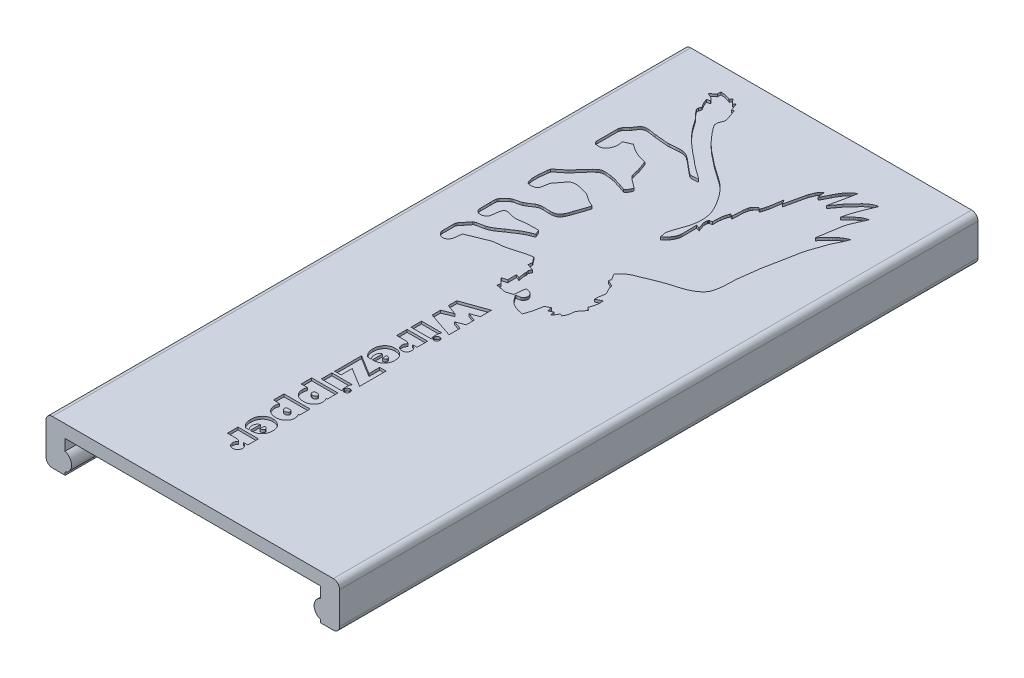
SolidWorks part; units mm, degrees
ref_plane "Front Plane" through (0, 0, 0) normal (0, 0, 1) x (1, 0, 0)
ref_plane "Top Plane" through (0, 0, 0) normal (0, 1, 0) x (1, 0, 0)
ref_plane "Right Plane" through (0, 0, 0) normal (1, 0, 0) x (0, 0, -1)
sketch "Sketch1" plane through (0, 0, 0) normal (0, 0, 1) x (1, 0, 0)
  line L0 (21.5, 0) -> (22.5, 0)
  line L1 (0.5, 0) -> (1.5, 0)
  line L2 (0, 0.5) -> (0, 3)
  line L3 (0.5, 3.5) -> (22.5, 3.5)
  line L4 (23, 0.5) -> (23, 3)
  line L5 (1.5, 2.5) -> (21.5, 2.5)
  line L6 (1.5, 2.5) -> (1.5, 1.637)
  line L8 (21.5, 2.5) -> (21.5, 1.637)
  line L9 (1.5, 0.2228) -> (1.5, 0)
  line L10 (1.25, 0.9299) -> (21.75, 0.9299) construction
  line L11 (21.5, 0.2228) -> (21.5, 0)
  arc A1 (1.5, 0.2228) -> (1.5, 1.637) centre (1.25, 0.9299) ccw
  arc A2 (21.5, 1.637) -> (21.5, 0.2228) centre (21.75, 0.9299) ccw
  arc A3 (23, 3) -> (22.5, 3.5) centre (22.5, 3) ccw
  arc A4 (0.5, 3.5) -> (0, 3) centre (0.5, 3) ccw
  arc A5 (23, 0.5) -> (22.5, 0) centre (22.5, 0.5) cw
  arc A6 (0, 0.5) -> (0.5, 0) centre (0.5, 0.5) ccw
  point P9 (11.5, 2.5)
  point P10 (11.5, 3.5)
  point P11 (0, 1.75)
  point P20 (23, 3.5)
  point P23 (0, 3.5)
  point P28 (0, 0)
  dimension "D6" = 1.5
  dimension "D9" = 0.5
  dimension "D10" = 0.5
  dimension "D1" = 23
  dimension "D2" = 3.5
  dimension "D3" = 1
  dimension "D4" = 1.5
  dimension "D5" = 20
  dimension "D7" = 0.25
  dimension "D8" = 0.25
extrude "Boss-Extrude1" add sketch "Sketch1" along normal blind 50
sketch "Sketch2" plane through (0, 3.5, -61.2632) normal (0, 1, 0) x (1, 0, 0)
  line L4 (19.7713, -68.0162) -> (19.7056, -68.0387)
  line L5 (19.7056, -68.0387) -> (19.6414, -68.0638)
  line L6 (19.6414, -68.0638) -> (19.5786, -68.0912)
  line L7 (19.5786, -68.0912) -> (19.5173, -68.1208)
  line L8 (19.5173, -68.1208) -> (19.4572, -68.1527)
  line L9 (19.4572, -68.1527) -> (19.3985, -68.1865)
  line L10 (19.3985, -68.1865) -> (19.341, -68.2223)
  line L11 (19.341, -68.2223) -> (19.2846, -68.2598)
  line L12 (19.2846, -68.2598) -> (19.2294, -68.2991)
  line L13 (19.2294, -68.2991) -> (19.1752, -68.34)
  line L14 (19.1752, -68.34) -> (19.122, -68.3824)
  line L15 (19.122, -68.3824) -> (19.0697, -68.4261)
  line L16 (19.0697, -68.4261) -> (19.0184, -68.4711)
  line L17 (19.0184, -68.4711) -> (18.918, -68.5644)
  line L18 (18.918, -68.5644) -> (18.7727, -68.711)
  line L19 (18.7727, -68.711) -> (18.2698, -69.2714)
  line L20 (18.2698, -69.2714) -> (18.2812, -69.1529)
  line L21 (18.2812, -69.1529) -> (18.535, -67.5691)
  line L22 (18.535, -67.5691) -> (18.544, -67.5095)
  line L23 (18.544, -67.5095) -> (18.5547, -67.4504)
  line L24 (18.5547, -67.4504) -> (18.567, -67.3918)
  line L25 (18.567, -67.3918) -> (18.5808, -67.3338)
  line L26 (18.5808, -67.3338) -> (18.6125, -67.2189)
  line L27 (18.6125, -67.2189) -> (18.649, -67.1057)
  line L28 (18.649, -67.1057) -> (18.7112, -66.9383)
  line L29 (18.7112, -66.9383) -> (19.0474, -66.172)
  line L30 (19.0474, -66.172) -> (19.1337, -65.9499)
  line L31 (19.1337, -65.9499) -> (19.0766, -65.96)
  line L32 (19.0766, -65.96) -> (19.021, -65.9729)
  line L33 (19.021, -65.9729) -> (18.9668, -65.9885)
  line L34 (18.9668, -65.9885) -> (18.9139, -66.0067)
  line L35 (18.9139, -66.0067) -> (18.8624, -66.0273)
  line L36 (18.8624, -66.0273) -> (18.812, -66.0502)
  line L37 (18.812, -66.0502) -> (18.7628, -66.0753)
  line L38 (18.7628, -66.0753) -> (18.7147, -66.1024)
  line L39 (18.7147, -66.1024) -> (18.6677, -66.1313)
  line L40 (18.6677, -66.1313) -> (18.6216, -66.1621)
  line L41 (18.6216, -66.1621) -> (18.5764, -66.1944)
  line L42 (18.5764, -66.1944) -> (18.5321, -66.2282)
  line L43 (18.5321, -66.2282) -> (18.4458, -66.2997)
  line L44 (18.4458, -66.2997) -> (18.3621, -66.3754)
  line L45 (18.3621, -66.3754) -> (18.2006, -66.5354)
  line L46 (18.2006, -66.5354) -> (17.8477, -66.8963)
  line L47 (17.8477, -66.8963) -> (17.8847, -66.737)
  line L48 (17.8847, -66.737) -> (17.9683, -66.4211)
  line L49 (17.9683, -66.4211) -> (18.0638, -66.1089)
  line L50 (18.0638, -66.1089) -> (18.226, -65.6467)
  line L51 (18.226, -65.6467) -> (18.633, -64.6662)
  line L52 (18.633, -64.6662) -> (18.5994, -64.6698)
  line L53 (18.5994, -64.6698) -> (18.5332, -64.6806)
  line L54 (18.5332, -64.6806) -> (18.4685, -64.6959)
  line L55 (18.4685, -64.6959) -> (18.4051, -64.7155)
  line L56 (18.4051, -64.7155) -> (18.3126, -64.752)
  line L57 (18.3126, -64.752) -> (18.2231, -64.7961)
  line L58 (18.2231, -64.7961) -> (18.0805, -64.8835)
  line L59 (18.0805, -64.8835) -> (17.7942, -65.1134)
  line L60 (17.7942, -65.1134) -> (17.0691, -65.9091)
  line L61 (17.0691, -65.9091) -> (16.8287, -66.2416)
  line L62 (16.8287, -66.2416) -> (16.513, -66.6563)
  line L63 (16.513, -66.6563) -> (16.7942, -65.369)
  line L64 (16.7942, -65.369) -> (16.9419, -64.5963)
  line L65 (16.9419, -64.5963) -> (16.8708, -64.6363)
  line L66 (16.8708, -64.6363) -> (16.8028, -64.6792)
  line L67 (16.8028, -64.6792) -> (16.7378, -64.7251)
  line L68 (16.7378, -64.7251) -> (16.6757, -64.7737)
  line L69 (16.6757, -64.7737) -> (16.6162, -64.8249)
  line L70 (16.6162, -64.8249) -> (16.5593, -64.8785)
  line L71 (16.5593, -64.8785) -> (16.5048, -64.9343)
  line L72 (16.5048, -64.9343) -> (16.4525, -64.9923)
  line L73 (16.4525, -64.9923) -> (16.4023, -65.0522)
  line L74 (16.4023, -65.0522) -> (16.3541, -65.114)
  line L75 (16.3541, -65.114) -> (16.3077, -65.1774)
  line L76 (16.3077, -65.1774) -> (16.263, -65.2423)
  line L77 (16.263, -65.2423) -> (16.2198, -65.3086)
  line L78 (16.2198, -65.3086) -> (16.178, -65.3761)
  line L79 (16.178, -65.3761) -> (16.0979, -65.514)
  line L80 (16.0979, -65.514) -> (15.9845, -65.7262)
  line L81 (15.9845, -65.7262) -> (15.694, -66.2934)
  line L82 (15.694, -66.2934) -> (15.6177, -66.4289)
  line L83 (15.6177, -66.4289) -> (15.549, -65.8484)
  line L84 (15.549, -65.8484) -> (15.5225, -65.8651)
  line L85 (15.5225, -65.8651) -> (15.4723, -65.9013)
  line L86 (15.4723, -65.9013) -> (15.426, -65.9412)
  line L87 (15.426, -65.9412) -> (15.3833, -65.9844)
  line L88 (15.3833, -65.9844) -> (15.3439, -66.0306)
  line L89 (15.3439, -66.0306) -> (15.2905, -66.1046)
  line L90 (15.2905, -66.1046) -> (15.2284, -66.2106)
  line L91 (15.2284, -66.2106) -> (15.0765, -66.58)
  line L92 (15.0765, -66.58) -> (15.0409, -66.6935)
  line L93 (15.0409, -66.6935) -> (14.6863, -68.2584)
  line L94 (14.6863, -68.2584) -> (14.4749, -67.9375)
  line L95 (14.4749, -67.9375) -> (14.4456, -68.1048)
  line L96 (14.4456, -68.1048) -> (14.3106, -68.9476)
  line L97 (14.3106, -68.9476) -> (14.2712, -69.1132)
  line L98 (14.2712, -69.1132) -> (14.24, -69.2224)
  line L99 (14.24, -69.2224) -> (14.2042, -69.3303)
  line L100 (14.2042, -69.3303) -> (14.1631, -69.4368)
  line L101 (14.1631, -69.4368) -> (14.1404, -69.4895)
  line L102 (14.1404, -69.4895) -> (14.1161, -69.5418)
  line L103 (14.1161, -69.5418) -> (13.9814, -69.4095)
  line L104 (13.9814, -69.4095) -> (13.7581, -69.6328)
  line L105 (13.7581, -69.6328) -> (13.6767, -69.7542)
  line L106 (13.6767, -69.7542) -> (13.6425, -69.8308)
  line L107 (13.6425, -69.8308) -> (13.6243, -69.8924)
  line L108 (13.6243, -69.8924) -> (13.6148, -69.9324)
  line L109 (13.6148, -69.9324) -> (13.592, -70.0527)
  line L110 (13.592, -70.0527) -> (13.5689, -70.255)
  line L111 (13.5689, -70.255) -> (13.5297, -71.0705)
  line L112 (13.5297, -71.0705) -> (13.3341, -70.9606)
  line L113 (13.3341, -70.9606) -> (13.3022, -71.0425)
  line L114 (13.3022, -71.0425) -> (13.248, -71.2091)
  line L115 (13.248, -71.2091) -> (13.2062, -71.3788)
  line L116 (13.2062, -71.3788) -> (13.1698, -71.5941)
  line L117 (13.1698, -71.5941) -> (13.1475, -71.8557)
  line L118 (13.1475, -71.8557) -> (13.1495, -72.206)
  line L119 (13.1495, -72.206) -> (12.9637, -72.2453)
  line L120 (12.9637, -72.2453) -> (12.9195, -72.274)
  line L121 (12.9195, -72.274) -> (12.8989, -72.299)
  line L122 (12.8989, -72.299) -> (12.8883, -72.3195)
  line L123 (12.8883, -72.3195) -> (12.8805, -72.3435)
  line L124 (12.8805, -72.3435) -> (12.874, -72.3729)
  line L125 (12.874, -72.3729) -> (12.8656, -72.4318)
  line L126 (12.8656, -72.4318) -> (12.8625, -72.4903)
  line L127 (12.8625, -72.4903) -> (12.8643, -72.5487)
  line L128 (12.8643, -72.5487) -> (12.8705, -72.6068)
  line L129 (12.8705, -72.6068) -> (12.8937, -72.722)
  line L130 (12.8937, -72.722) -> (13.0558, -73.168)
  line L131 (13.0558, -73.168) -> (12.7626, -73.0589)
  line L132 (12.7626, -73.0589) -> (12.7728, -74.2235)
  line L133 (12.7728, -74.2235) -> (12.7694, -74.268)
  line L134 (12.7694, -74.268) -> (12.7642, -74.3119)
  line L135 (12.7642, -74.3119) -> (12.7573, -74.3554)
  line L136 (12.7573, -74.3554) -> (12.7487, -74.3983)
  line L137 (12.7487, -74.3983) -> (12.7384, -74.4406)
  line L138 (12.7384, -74.4406) -> (12.7265, -74.4825)
  line L139 (12.7265, -74.4825) -> (12.7131, -74.5237)
  line L140 (12.7131, -74.5237) -> (12.6982, -74.5644)
  line L141 (12.6982, -74.5644) -> (12.6819, -74.6046)
  line L142 (12.6819, -74.6046) -> (12.6642, -74.6441)
  line L143 (12.6642, -74.6441) -> (12.6248, -74.7214)
  line L144 (12.6248, -74.7214) -> (12.5806, -74.7963)
  line L145 (12.5806, -74.7963) -> (12.5319, -74.8686)
  line L146 (12.5319, -74.8686) -> (12.4791, -74.9384)
  line L147 (12.4791, -74.9384) -> (12.4226, -75.0055)
  line L148 (12.4226, -75.0055) -> (12.332, -75.1011)
  line L149 (12.332, -75.1011) -> (12.2356, -75.1902)
  line L150 (12.2356, -75.1902) -> (12.1347, -75.2728)
  line L151 (12.1347, -75.2728) -> (12.0463, -74.8208)
  line L152 (12.0463, -74.8208) -> (12.0572, -74.7514)
  line L153 (12.0572, -74.7514) -> (12.0701, -74.6825)
  line L154 (12.0701, -74.6825) -> (12.0846, -74.6141)
  line L155 (12.0846, -74.6141) -> (12.1008, -74.546)
  line L156 (12.1008, -74.546) -> (12.1374, -74.4111)
  line L157 (12.1374, -74.4111) -> (12.2004, -74.2109)
  line L158 (12.2004, -74.2109) -> (12.4552, -73.4833)
  line L159 (12.4552, -73.4833) -> (12.4951, -73.3494)
  line L160 (12.4951, -73.3494) -> (12.5302, -73.2142)
  line L161 (12.5302, -73.2142) -> (12.5455, -73.1461)
  line L162 (12.5455, -73.1461) -> (12.5591, -73.0775)
  line L163 (12.5591, -73.0775) -> (12.5709, -73.0084)
  line L164 (12.5709, -73.0084) -> (12.5807, -72.9388)
  line L165 (12.5807, -72.9388) -> (12.5884, -72.8687)
  line L166 (12.5884, -72.8687) -> (12.5946, -72.8106)
  line L167 (12.5946, -72.8106) -> (12.6038, -72.6941)
  line L168 (12.6038, -72.6941) -> (12.6085, -72.5773)
  line L169 (12.6085, -72.5773) -> (12.6087, -72.4603)
  line L170 (12.6087, -72.4603) -> (12.6042, -72.3433)
  line L171 (12.6042, -72.3433) -> (12.5951, -72.2267)
  line L172 (12.5951, -72.2267) -> (12.5813, -72.1106)
  line L173 (12.5813, -72.1106) -> (12.5626, -71.9952)
  line L174 (12.5626, -71.9952) -> (12.5392, -71.8808)
  line L175 (12.5392, -71.8808) -> (12.5108, -71.7675)
  line L176 (12.5108, -71.7675) -> (12.4775, -71.6556)
  line L177 (12.4775, -71.6556) -> (12.4392, -71.5453)
  line L178 (12.4392, -71.5453) -> (12.3958, -71.4368)
  line L179 (12.3958, -71.4368) -> (12.3473, -71.3303)
  line L180 (12.3473, -71.3303) -> (12.2936, -71.2261)
  line L181 (12.2936, -71.2261) -> (12.1536, -70.9726)
  line L182 (12.1536, -70.9726) -> (12.0556, -70.8056)
  line L183 (12.0556, -70.8056) -> (11.9537, -70.6406)
  line L184 (11.9537, -70.6406) -> (11.8476, -70.4782)
  line L185 (11.8476, -70.4782) -> (11.7372, -70.3187)
  line L186 (11.7372, -70.3187) -> (11.6223, -70.1625)
  line L187 (11.6223, -70.1625) -> (11.5631, -70.0859)
  line L188 (11.5631, -70.0859) -> (11.5027, -70.0102)
  line L189 (11.5027, -70.0102) -> (11.441, -69.9356)
  line L190 (11.441, -69.9356) -> (11.3782, -69.8621)
  line L191 (11.3782, -69.8621) -> (11.3141, -69.7897)
  line L192 (11.3141, -69.7897) -> (11.2486, -69.7186)
  line L193 (11.2486, -69.7186) -> (11.1819, -69.6487)
  line L194 (11.1819, -69.6487) -> (11.1139, -69.5802)
  line L195 (11.1139, -69.5802) -> (11.0445, -69.513)
  line L196 (11.0445, -69.513) -> (10.9737, -69.4473)
  line L197 (10.9737, -69.4473) -> (10.9015, -69.383)
  line L198 (10.9015, -69.383) -> (10.8279, -69.3203)
  line L199 (10.8279, -69.3203) -> (10.7528, -69.2592)
  line L200 (10.7528, -69.2592) -> (10.6763, -69.1997)
  line L201 (10.6763, -69.1997) -> (10.5982, -69.1419)
  line L202 (10.5982, -69.1419) -> (10.5187, -69.0859)
  line L203 (10.5187, -69.0859) -> (9.4452, -68.33)
  line L204 (9.4452, -68.33) -> (9.3773, -68.2867)
  line L205 (9.3773, -68.2867) -> (8.53, -67.6115)
  line L206 (8.53, -67.6115) -> (8.3361, -67.4547)
  line L207 (8.3361, -67.4547) -> (8.1475, -67.2919)
  line L208 (8.1475, -67.2919) -> (7.9041, -67.0658)
  line L209 (7.9041, -67.0658) -> (7.6696, -66.8305)
  line L210 (7.6696, -66.8305) -> (7.4436, -66.5867)
  line L211 (7.4436, -66.5867) -> (7.173, -66.2715)
  line L212 (7.173, -66.2715) -> (6.8648, -65.88)
  line L213 (6.8648, -65.88) -> (6.7097, -65.6569)
  line L214 (6.7097, -65.6569) -> (6.6566, -65.5438)
  line L215 (6.6566, -65.5438) -> (6.6407, -65.4743)
  line L216 (6.6407, -65.4743) -> (6.638, -65.4193)
  line L217 (6.638, -65.4193) -> (6.637, -65.3934)
  line L218 (6.637, -65.3934) -> (6.6379, -65.3678)
  line L219 (6.6379, -65.3678) -> (6.6403, -65.3423)
  line L220 (6.6403, -65.3423) -> (6.6494, -65.2922)
  line L221 (6.6494, -65.2922) -> (6.6631, -65.2427)
  line L222 (6.6631, -65.2427) -> (6.7675, -64.9759)
  line L223 (6.7675, -64.9759) -> (6.7877, -64.9024)
  line L224 (6.7877, -64.9024) -> (6.7953, -64.8526)
  line L225 (6.7953, -64.8526) -> (6.7968, -64.8275)
  line L226 (6.7968, -64.8275) -> (6.7967, -64.8021)
  line L227 (6.7967, -64.8021) -> (6.7947, -64.7765)
  line L228 (6.7947, -64.7765) -> (6.7907, -64.7506)
  line L229 (6.7907, -64.7506) -> (6.7846, -64.7245)
  line L230 (6.7846, -64.7245) -> (6.7763, -64.698)
  line L231 (6.7763, -64.698) -> (6.4789, -63.8339)
  line L232 (6.4789, -63.8339) -> (6.3162, -63.8719)
  line L233 (6.3162, -63.8719) -> (6.0814, -63.2667)
  line L234 (6.0814, -63.2667) -> (5.9437, -63.4423)
  line L235 (5.9437, -63.4423) -> (5.6179, -63.0803)
  line L236 (5.6179, -63.0803) -> (5.4993, -63.2471)
  line L237 (5.4993, -63.2471) -> (5.4182, -63.2127)
  line L238 (5.4182, -63.2127) -> (5.0832, -63.1098)
  line L239 (5.0832, -63.1098) -> (4.852, -63.0789)
  line L240 (4.852, -63.0789) -> (4.6755, -63.0793)
  line L241 (4.6755, -63.0793) -> (4.6672, -63.3323)
  line L242 (4.6672, -63.3323) -> (4.3029, -63.6837)
  line L243 (4.3029, -63.6837) -> (4.4364, -63.7454)
  line L244 (4.4364, -63.7454) -> (4.6822, -63.862)
  line L245 (4.6822, -63.862) -> (4.7406, -63.904)
  line L246 (4.7406, -63.904) -> (4.7757, -63.9362)
  line L247 (4.7757, -63.9362) -> (4.8071, -63.9724)
  line L248 (4.8071, -63.9724) -> (4.8213, -63.9922)
  line L249 (4.8213, -63.9922) -> (4.8345, -64.0131)
  line L250 (4.8345, -64.0131) -> (4.8464, -64.0354)
  line L251 (4.8464, -64.0354) -> (4.8571, -64.059)
  line L252 (4.8571, -64.059) -> (4.8666, -64.0839)
  line L253 (4.8666, -64.0839) -> (4.6194, -64.1381)
  line L254 (4.6194, -64.1381) -> (4.6364, -64.2183)
  line L255 (4.6364, -64.2183) -> (4.6966, -64.3979)
  line L256 (4.6966, -64.3979) -> (4.9547, -64.8424)
  line L257 (4.9547, -64.8424) -> (4.8825, -65.0571)
  line L258 (4.8825, -65.0571) -> (4.8809, -65.1758)
  line L259 (4.8809, -65.1758) -> (4.9013, -65.2205)
  line L260 (4.9013, -65.2205) -> (4.9626, -65.3253)
  line L261 (4.9626, -65.3253) -> (5.3289, -65.7142)
  line L262 (5.3289, -65.7142) -> (5.3543, -65.7372)
  line L263 (5.3543, -65.7372) -> (5.4262, -65.8098)
  line L264 (5.4262, -65.8098) -> (5.5342, -65.9403)
  line L265 (5.5342, -65.9403) -> (5.9242, -66.4974)
  line L266 (5.9242, -66.4974) -> (5.9941, -66.5912)
  line L267 (5.9941, -66.5912) -> (6.0655, -66.6837)
  line L268 (6.0655, -66.6837) -> (6.1382, -66.7749)
  line L269 (6.1382, -66.7749) -> (6.2123, -66.8649)
  line L270 (6.2123, -66.8649) -> (6.2877, -66.9537)
  line L271 (6.2877, -66.9537) -> (6.3643, -67.0414)
  line L272 (6.3643, -67.0414) -> (6.4422, -67.128)
  line L273 (6.4422, -67.128) -> (6.5212, -67.2135)
  line L274 (6.5212, -67.2135) -> (6.6012, -67.2979)
  line L275 (6.6012, -67.2979) -> (6.7645, -67.4639)
  line L276 (6.7645, -67.4639) -> (6.9315, -67.6263)
  line L277 (6.9315, -67.6263) -> (7.102, -67.7852)
  line L278 (7.102, -67.7852) -> (7.2754, -67.9411)
  line L279 (7.2754, -67.9411) -> (7.5403, -68.1699)
  line L280 (7.5403, -68.1699) -> (8.3562, -68.8291)
  line L281 (8.3562, -68.8291) -> (8.3997, -68.8707)
  line L282 (8.3997, -68.8707) -> (8.4887, -68.9512)
  line L283 (8.4887, -68.9512) -> (8.6269, -69.0657)
  line L284 (8.6269, -69.0657) -> (8.9149, -69.2793)
  line L285 (8.9149, -69.2793) -> (9.5957, -69.7675)
  line L286 (9.5957, -69.7675) -> (9.7335, -69.883)
  line L287 (9.7335, -69.883) -> (9.2384, -69.9121)
  line L288 (9.2384, -69.9121) -> (9.1226, -69.8981)
  line L289 (9.1226, -69.8981) -> (9.0543, -69.8802)
  line L290 (9.0543, -69.8802) -> (8.9059, -69.7676)
  line L291 (8.9059, -69.7676) -> (7.9015, -68.9336)
  line L292 (7.9015, -68.9336) -> (7.6513, -68.7497)
  line L293 (7.6513, -68.7497) -> (7.6022, -68.7188)
  line L294 (7.6022, -68.7188) -> (7.5523, -68.6913)
  line L295 (7.5523, -68.6913) -> (7.5017, -68.667)
  line L296 (7.5017, -68.667) -> (7.4505, -68.6458)
  line L297 (7.4505, -68.6458) -> (7.3986, -68.6275)
  line L298 (7.3986, -68.6275) -> (7.3462, -68.612)
  line L299 (7.3462, -68.612) -> (7.2932, -68.599)
  line L300 (7.2932, -68.599) -> (7.2397, -68.5885)
  line L301 (7.2397, -68.5885) -> (7.1858, -68.5802)
  line L302 (7.1858, -68.5802) -> (7.1315, -68.5739)
  line L303 (7.1315, -68.5739) -> (7.0768, -68.5696)
  line L304 (7.0768, -68.5696) -> (7.0217, -68.5671)
  line L305 (7.0217, -68.5671) -> (6.9108, -68.5665)
  line L306 (6.9108, -68.5665) -> (6.7431, -68.5748)
  line L307 (6.7431, -68.5748) -> (6.1852, -68.6265)
  line L308 (6.1852, -68.6265) -> (6.0763, -68.6314)
  line L309 (6.0763, -68.6314) -> (4.992, -68.5326)
  line L310 (4.992, -68.5326) -> (4.8611, -68.5147)
  line L311 (4.8611, -68.5147) -> (4.3666, -68.4393)
  line L312 (4.3666, -68.4393) -> (4.2677, -68.4378)
  line L313 (4.2677, -68.4378) -> (4.2019, -68.4418)
  line L314 (4.2019, -68.4418) -> (4.1362, -68.4506)
  line L315 (4.1362, -68.4506) -> (4.0706, -68.4648)
  line L316 (4.0706, -68.4648) -> (4.0379, -68.4741)
  line L317 (4.0379, -68.4741) -> (4.014, -68.4828)
  line L318 (4.014, -68.4828) -> (3.9912, -68.4926)
  line L319 (3.9912, -68.4926) -> (3.9694, -68.5037)
  line L320 (3.9694, -68.5037) -> (3.9287, -68.5289)
  line L321 (3.9287, -68.5289) -> (3.8914, -68.5581)
  line L322 (3.8914, -68.5581) -> (3.857, -68.5905)
  line L323 (3.857, -68.5905) -> (3.7809, -68.6828)
  line L324 (3.7809, -68.6828) -> (3.575, -68.9832)
  line L325 (3.575, -68.9832) -> (3.5102, -69.0651)
  line L326 (3.5102, -69.0651) -> (3.2556, -69.3376)
  line L327 (3.2556, -69.3376) -> (3.2114, -69.4017)
  line L328 (3.2114, -69.4017) -> (3.1867, -69.4471)
  line L329 (3.1867, -69.4471) -> (3.1668, -69.4951)
  line L330 (3.1668, -69.4951) -> (3.1589, -69.5201)
  line L331 (3.1589, -69.5201) -> (3.1524, -69.5459)
  line L332 (3.1524, -69.5459) -> (3.1474, -69.5726)
  line L333 (3.1474, -69.5726) -> (3.144, -69.6001)
  line L334 (3.144, -69.6001) -> (3.14, -69.6565)
  line L335 (3.14, -69.6565) -> (3.1406, -71.2386)
  line L336 (3.1406, -71.2386) -> (3.1441, -71.2775)
  line L337 (3.1441, -71.2775) -> (3.1837, -71.4053)
  line L338 (3.1837, -71.4053) -> (3.2293, -71.4697)
  line L339 (3.2293, -71.4697) -> (3.2692, -71.5026)
  line L340 (3.2692, -71.5026) -> (3.3044, -71.5205)
  line L341 (3.3044, -71.5205) -> (3.3442, -71.5313)
  line L342 (3.3442, -71.5313) -> (3.6184, -71.552)
  line L343 (3.6184, -71.552) -> (3.7097, -71.5433)
  line L344 (3.7097, -71.5433) -> (3.7753, -71.5281)
  line L345 (3.7753, -71.5281) -> (3.8171, -71.513)
  line L346 (3.8171, -71.513) -> (3.857, -71.4934)
  line L347 (3.857, -71.4934) -> (3.8945, -71.4689)
  line L348 (3.8945, -71.4689) -> (3.9123, -71.4547)
  line L349 (3.9123, -71.4547) -> (3.9294, -71.4391)
  line L350 (3.9294, -71.4391) -> (3.9457, -71.422)
  line L351 (3.9457, -71.422) -> (3.9613, -71.4035)
  line L352 (3.9613, -71.4035) -> (3.9894, -71.3736)
  line L353 (3.9894, -71.3736) -> (4.0159, -71.3428)
  line L354 (4.0159, -71.3428) -> (4.0409, -71.3111)
  line L355 (4.0409, -71.3111) -> (4.0643, -71.2784)
  line L356 (4.0643, -71.2784) -> (4.0862, -71.2449)
  line L357 (4.0862, -71.2449) -> (4.1066, -71.2106)
  line L358 (4.1066, -71.2106) -> (4.1255, -71.1756)
  line L359 (4.1255, -71.1756) -> (4.1429, -71.1399)
  line L360 (4.1429, -71.1399) -> (4.1588, -71.1035)
  line L361 (4.1588, -71.1035) -> (4.1732, -71.0666)
  line L362 (4.1732, -71.0666) -> (4.1862, -71.0291)
  line L363 (4.1862, -71.0291) -> (4.1977, -70.9912)
  line L364 (4.1977, -70.9912) -> (4.2078, -70.9528)
  line L365 (4.2078, -70.9528) -> (4.2164, -70.914)
  line L366 (4.2164, -70.914) -> (4.2236, -70.8749)
  line L367 (4.2236, -70.8749) -> (4.2338, -70.7958)
  line L368 (4.2338, -70.7958) -> (4.2385, -70.7161)
  line L369 (4.2385, -70.7161) -> (4.2376, -70.636)
  line L370 (4.2376, -70.636) -> (4.2314, -70.556)
  line L371 (4.2314, -70.556) -> (4.2198, -70.4765)
  line L372 (4.2198, -70.4765) -> (4.203, -70.3979)
  line L373 (4.203, -70.3979) -> (4.181, -70.3206)
  line L374 (4.181, -70.3206) -> (4.7901, -70.0484)
  line L375 (4.7901, -70.0484) -> (5.2245, -70.3466)
  line L376 (5.2245, -70.3466) -> (5.4751, -70.4867)
  line L377 (5.4751, -70.4867) -> (5.6484, -70.5673)
  line L378 (5.6484, -70.5673) -> (5.7819, -70.6197)
  line L379 (5.7819, -70.6197) -> (5.9186, -70.6643)
  line L380 (5.9186, -70.6643) -> (6.0116, -70.6894)
  line L381 (6.0116, -70.6894) -> (6.4412, -70.8042)
  line L382 (6.4412, -70.8042) -> (6.6803, -71.4735)
  line L383 (6.6803, -71.4735) -> (6.7004, -71.5284)
  line L384 (6.7004, -71.5284) -> (6.7442, -71.699)
  line L385 (6.7442, -71.699) -> (6.8306, -72.1014)
  line L386 (6.8306, -72.1014) -> (6.8618, -72.1829)
  line L387 (6.8618, -72.1829) -> (6.8877, -72.2354)
  line L388 (6.8877, -72.2354) -> (6.9183, -72.2862)
  line L389 (6.9183, -72.2862) -> (6.9701, -72.3445)
  line L390 (6.9701, -72.3445) -> (7.1086, -72.4804)
  line L391 (7.1086, -72.4804) -> (7.7939, -72.9919)
  line L392 (7.7939, -72.9919) -> (7.7351, -73.1517)
  line L393 (7.7351, -73.1517) -> (7.6452, -73.3187)
  line L394 (7.6452, -73.3187) -> (7.5925, -73.3834)
  line L395 (7.5925, -73.3834) -> (7.5465, -73.4263)
  line L396 (7.5465, -73.4263) -> (7.4942, -73.4637)
  line L397 (7.4942, -73.4637) -> (7.4555, -73.4852)
  line L398 (7.4555, -73.4852) -> (6.9853, -73.3177)
  line L399 (6.9853, -73.3177) -> (6.4139, -73.1402)
  line L400 (6.4139, -73.1402) -> (6.2188, -73.0984)
  line L401 (6.2188, -73.0984) -> (6.0703, -73.0755)
  line L402 (6.0703, -73.0755) -> (6.002, -73.0661)
  line L403 (6.002, -73.0661) -> (5.6117, -73.0217)
  line L404 (5.6117, -73.0217) -> (5.5053, -73.0221)
  line L405 (5.5053, -73.0221) -> (5.4354, -73.0278)
  line L406 (5.4354, -73.0278) -> (5.3668, -73.0388)
  line L407 (5.3668, -73.0388) -> (5.3331, -73.0464)
  line L408 (5.3331, -73.0464) -> (5.2997, -73.0557)
  line L409 (5.2997, -73.0557) -> (5.2669, -73.0666)
  line L410 (5.2669, -73.0666) -> (5.2345, -73.0793)
  line L411 (5.2345, -73.0793) -> (5.2027, -73.0938)
  line L412 (5.2027, -73.0938) -> (5.1715, -73.1103)
  line L413 (5.1715, -73.1103) -> (5.1409, -73.1288)
  line L414 (5.1409, -73.1288) -> (5.111, -73.1495)
  line L415 (5.111, -73.1495) -> (5.0818, -73.1724)
  line L416 (5.0818, -73.1724) -> (5.0388, -73.2082)
  line L417 (5.0388, -73.2082) -> (4.9143, -73.3196)
  line L418 (4.9143, -73.3196) -> (4.7183, -73.5171)
  line L419 (4.7183, -73.5171) -> (3.986, -74.3579)
  line L420 (3.986, -74.3579) -> (3.4335, -74.7985)
  line L421 (3.4335, -74.7985) -> (3.2432, -74.9884)
  line L422 (3.2432, -74.9884) -> (3.2042, -75.1321)
  line L423 (3.2042, -75.1321) -> (3.1326, -75.8459)
  line L424 (3.1326, -75.8459) -> (3.1308, -76.2528)
  line L425 (3.1308, -76.2528) -> (3.1487, -76.422)
  line L426 (3.1487, -76.422) -> (3.1689, -76.5211)
  line L427 (3.1689, -76.5211) -> (3.1872, -76.5856)
  line L428 (3.1872, -76.5856) -> (3.2098, -76.6487)
  line L429 (3.2098, -76.6487) -> (3.2373, -76.71)
  line L430 (3.2373, -76.71) -> (3.2699, -76.7694)
  line L431 (3.2699, -76.7694) -> (3.2883, -76.7983)
  line L432 (3.2883, -76.7983) -> (3.3292, -76.819)
  line L433 (3.3292, -76.819) -> (3.3932, -76.8429)
  line L434 (3.3932, -76.8429) -> (3.4598, -76.8586)
  line L435 (3.4598, -76.8586) -> (3.5512, -76.8679)
  line L436 (3.5512, -76.8679) -> (3.644, -76.8649)
  line L437 (3.644, -76.8649) -> (3.7814, -76.8404)
  line L438 (3.7814, -76.8404) -> (3.9314, -76.7866)
  line L439 (3.9314, -76.7866) -> (3.9502, -76.7698)
  line L440 (3.9502, -76.7698) -> (3.9676, -76.7523)
  line L441 (3.9676, -76.7523) -> (3.9837, -76.7339)
  line L442 (3.9837, -76.7339) -> (4.012, -76.6951)
  line L443 (4.012, -76.6951) -> (4.0358, -76.6537)
  line L444 (4.0358, -76.6537) -> (4.0557, -76.6102)
  line L445 (4.0557, -76.6102) -> (4.0855, -76.5179)
  line L446 (4.0855, -76.5179) -> (4.1545, -76.1303)
  line L447 (4.1545, -76.1303) -> (4.1578, -76.0999)
  line L448 (4.1578, -76.0999) -> (4.1626, -76.0703)
  line L449 (4.1626, -76.0703) -> (4.169, -76.0415)
  line L450 (4.169, -76.0415) -> (4.1769, -76.0135)
  line L451 (4.1769, -76.0135) -> (4.1968, -75.9596)
  line L452 (4.1968, -75.9596) -> (4.2214, -75.9082)
  line L453 (4.2214, -75.9082) -> (4.2658, -75.8349)
  line L454 (4.2658, -75.8349) -> (4.4881, -75.5651)
  line L455 (4.4881, -75.5651) -> (4.5925, -75.4268)
  line L456 (4.5925, -75.4268) -> (4.7686, -75.1769)
  line L457 (4.7686, -75.1769) -> (4.8234, -75.1263)
  line L458 (4.8234, -75.1263) -> (4.8698, -75.0957)
  line L459 (4.8698, -75.0957) -> (4.9038, -75.0796)
  line L460 (4.9038, -75.0796) -> (4.9405, -75.0674)
  line L461 (4.9405, -75.0674) -> (4.9801, -75.0596)
  line L462 (4.9801, -75.0596) -> (5.022, -75.0473)
  line L463 (5.022, -75.0473) -> (5.0638, -75.037)
  line L464 (5.0638, -75.037) -> (5.1057, -75.0287)
  line L465 (5.1057, -75.0287) -> (5.1475, -75.0223)
  line L466 (5.1475, -75.0223) -> (5.1893, -75.0177)
  line L467 (5.1893, -75.0177) -> (5.2311, -75.0147)
  line L468 (5.2311, -75.0147) -> (5.2729, -75.0134)
  line L469 (5.2729, -75.0134) -> (5.3147, -75.0136)
  line L470 (5.3147, -75.0136) -> (5.3982, -75.018)
  line L471 (5.3982, -75.018) -> (5.4815, -75.0273)
  line L472 (5.4815, -75.0273) -> (5.6062, -75.0489)
  line L473 (5.6062, -75.0489) -> (6.1798, -75.2004)
  line L474 (6.1798, -75.2004) -> (6.2396, -75.2191)
  line L475 (6.2396, -75.2191) -> (6.297, -75.2424)
  line L476 (6.297, -75.2424) -> (6.379, -75.2844)
  line L477 (6.379, -75.2844) -> (6.5333, -75.3862)
  line L478 (6.5333, -75.3862) -> (6.8623, -75.6178)
  line L479 (6.8623, -75.6178) -> (6.945, -75.6597)
  line L480 (6.945, -75.6597) -> (7.3529, -75.8473)
  line L481 (7.3529, -75.8473) -> (7.3353, -75.9277)
  line L482 (7.3353, -75.9277) -> (7.2542, -76.2027)
  line L483 (7.2542, -76.2027) -> (6.9853, -76.977)
  line L484 (6.9853, -76.977) -> (6.9218, -77.1748)
  line L485 (6.9218, -77.1748) -> (6.8417, -77.3713)
  line L486 (6.8417, -77.3713) -> (6.7927, -77.4646)
  line L487 (6.7927, -77.4646) -> (6.7559, -77.5237)
  line L488 (6.7559, -77.5237) -> (6.7156, -77.5798)
  line L489 (6.7156, -77.5798) -> (6.6712, -77.6323)
  line L490 (6.6712, -77.6323) -> (6.6474, -77.657)
  line L491 (6.6474, -77.657) -> (6.6225, -77.6807)
  line L492 (6.6225, -77.6807) -> (6.5965, -77.7032)
  line L493 (6.5965, -77.7032) -> (6.5693, -77.7244)
  line L494 (6.5693, -77.7244) -> (6.5408, -77.7444)
  line L495 (6.5408, -77.7444) -> (6.5111, -77.7629)
  line L496 (6.5111, -77.7629) -> (6.48, -77.7801)
  line L497 (6.48, -77.7801) -> (6.4476, -77.7958)
  line L498 (6.4476, -77.7958) -> (6.4056, -77.8087)
  line L499 (6.4056, -77.8087) -> (6.3634, -77.8195)
  line L500 (6.3634, -77.8195) -> (6.3211, -77.8286)
  line L501 (6.3211, -77.8286) -> (6.2785, -77.8359)
  line L502 (6.2785, -77.8359) -> (6.2358, -77.8416)
  line L503 (6.2358, -77.8416) -> (6.15, -77.849)
  line L504 (6.15, -77.849) -> (6.0204, -77.8517)
  line L505 (6.0204, -77.8517) -> (5.5419, -77.8342)
  line L506 (5.5419, -77.8342) -> (5.4122, -77.8386)
  line L507 (5.4122, -77.8386) -> (5.3262, -77.8475)
  line L508 (5.3262, -77.8475) -> (5.2834, -77.8541)
  line L509 (5.2834, -77.8541) -> (5.2408, -77.8624)
  line L510 (5.2408, -77.8624) -> (5.1984, -77.8725)
  line L511 (5.1984, -77.8725) -> (5.1429, -77.8929)
  line L512 (5.1429, -77.8929) -> (5.0372, -77.9432)
  line L513 (5.0372, -77.9432) -> (4.5955, -78.2327)
  line L514 (4.5955, -78.2327) -> (4.4658, -78.3013)
  line L515 (4.4658, -78.3013) -> (4.4141, -78.3286)
  line L516 (4.4141, -78.3286) -> (4.3608, -78.3512)
  line L517 (4.3608, -78.3512) -> (4.2508, -78.3859)
  line L518 (4.2508, -78.3859) -> (3.8549, -78.4745)
  line L519 (3.8549, -78.4745) -> (3.7737, -78.504)
  line L520 (3.7737, -78.504) -> (3.7213, -78.5287)
  line L521 (3.7213, -78.5287) -> (3.6706, -78.5583)
  line L522 (3.6706, -78.5583) -> (3.6162, -78.5953)
  line L523 (3.6162, -78.5953) -> (3.2174, -79.0006)
  line L524 (3.2174, -79.0006) -> (3.1932, -79.0363)
  line L525 (3.1932, -79.0363) -> (3.1737, -79.0734)
  line L526 (3.1737, -79.0734) -> (3.1523, -79.1314)
  line L527 (3.1523, -79.1314) -> (3.1358, -79.2122)
  line L528 (3.1358, -79.2122) -> (3.1303, -79.5906)
  line L529 (3.1303, -79.5906) -> (3.1317, -79.6254)
  line L530 (3.1317, -79.6254) -> (3.1352, -80.3612)
  line L531 (3.1352, -80.3612) -> (3.1532, -80.4995)
  line L532 (3.1532, -80.4995) -> (3.1755, -80.6021)
  line L533 (3.1755, -80.6021) -> (3.1949, -80.6327)
  line L534 (3.1949, -80.6327) -> (3.2166, -80.6607)
  line L535 (3.2166, -80.6607) -> (3.2403, -80.6861)
  line L536 (3.2403, -80.6861) -> (3.2659, -80.7089)
  line L537 (3.2659, -80.7089) -> (3.2932, -80.7292)
  line L538 (3.2932, -80.7292) -> (3.322, -80.747)
  line L539 (3.322, -80.747) -> (3.3522, -80.7624)
  line L540 (3.3522, -80.7624) -> (3.3836, -80.7752)
  line L541 (3.3836, -80.7752) -> (3.416, -80.7857)
  line L542 (3.416, -80.7857) -> (3.4492, -80.7938)
  line L543 (3.4492, -80.7938) -> (3.4831, -80.7995)
  line L544 (3.4831, -80.7995) -> (3.5175, -80.8029)
  line L545 (3.5175, -80.8029) -> (3.5521, -80.8041)
  line L546 (3.5521, -80.8041) -> (3.587, -80.8029)
  line L547 (3.587, -80.8029) -> (3.6217, -80.7995)
  line L548 (3.6217, -80.7995) -> (3.6563, -80.7939)
  line L549 (3.6563, -80.7939) -> (3.6905, -80.7862)
  line L550 (3.6905, -80.7862) -> (3.7241, -80.7762)
  line L551 (3.7241, -80.7762) -> (3.757, -80.7642)
  line L552 (3.757, -80.7642) -> (3.789, -80.7501)
  line L553 (3.789, -80.7501) -> (3.8199, -80.7339)
  line L554 (3.8199, -80.7339) -> (3.8495, -80.7157)
  line L555 (3.8495, -80.7157) -> (3.8777, -80.6955)
  line L556 (3.8777, -80.6955) -> (3.9043, -80.6733)
  line L557 (3.9043, -80.6733) -> (3.9291, -80.6492)
  line L558 (3.9291, -80.6492) -> (3.9519, -80.6232)
  line L559 (3.9519, -80.6232) -> (3.9726, -80.5953)
  line L560 (3.9726, -80.5953) -> (3.991, -80.5656)
  line L561 (3.991, -80.5656) -> (4.0069, -80.534)
  line L562 (4.0069, -80.534) -> (4.0267, -80.4685)
  line L563 (4.0267, -80.4685) -> (4.042, -80.4016)
  line L564 (4.042, -80.4016) -> (4.0936, -79.9875)
  line L565 (4.0936, -79.9875) -> (4.1181, -79.852)
  line L566 (4.1181, -79.852) -> (4.136, -79.7861)
  line L567 (4.136, -79.7861) -> (4.1589, -79.7219)
  line L568 (4.1589, -79.7219) -> (4.1725, -79.6905)
  line L569 (4.1725, -79.6905) -> (4.1877, -79.6596)
  line L570 (4.1877, -79.6596) -> (4.2046, -79.6293)
  line L571 (4.2046, -79.6293) -> (4.2234, -79.5996)
  line L572 (4.2234, -79.5996) -> (4.2441, -79.5705)
  line L573 (4.2441, -79.5705) -> (4.2943, -79.56)
  line L574 (4.2943, -79.56) -> (4.3945, -79.5495)
  line L575 (4.3945, -79.5495) -> (4.519, -79.5532)
  line L576 (4.519, -79.5532) -> (4.957, -79.6603)
  line L577 (4.957, -79.6603) -> (4.9931, -79.6704)
  line L578 (4.9931, -79.6704) -> (5.0293, -79.6788)
  line L579 (5.0293, -79.6788) -> (5.0656, -79.6855)
  line L580 (5.0656, -79.6855) -> (5.1018, -79.6907)
  line L581 (5.1018, -79.6907) -> (5.1381, -79.6943)
  line L582 (5.1381, -79.6943) -> (5.2106, -79.6976)
  line L583 (5.2106, -79.6976) -> (5.2833, -79.6962)
  line L584 (5.2833, -79.6962) -> (5.3923, -79.6872)
  line L585 (5.3923, -79.6872) -> (5.9018, -79.6117)
  line L586 (5.9018, -79.6117) -> (6.0109, -79.6057)
  line L587 (6.0109, -79.6057) -> (6.9107, -79.5831)
  line L588 (6.9107, -79.5831) -> (7.08, -79.9797)
  line L589 (7.08, -79.9797) -> (6.9606, -80.0183)
  line L590 (6.9606, -80.0183) -> (6.8433, -80.0615)
  line L591 (6.8433, -80.0615) -> (6.7277, -80.1089)
  line L592 (6.7277, -80.1089) -> (6.5577, -80.187)
  line L593 (6.5577, -80.187) -> (6.3912, -80.2727)
  line L594 (6.3912, -80.2727) -> (6.1741, -80.3968)
  line L595 (6.1741, -80.3968) -> (5.4975, -80.8472)
  line L596 (5.4975, -80.8472) -> (5.0502, -81.1631)
  line L597 (5.0502, -81.1631) -> (4.8455, -81.2766)
  line L598 (4.8455, -81.2766) -> (4.7027, -81.3392)
  line L599 (4.7027, -81.3392) -> (4.5918, -81.3776)
  line L600 (4.5918, -81.3776) -> (4.5159, -81.3986)
  line L601 (4.5159, -81.3986) -> (3.9625, -81.5099)
  line L602 (3.9625, -81.5099) -> (3.8363, -81.554)
  line L603 (3.8363, -81.554) -> (3.7636, -81.5898)
  line L604 (3.7636, -81.5898) -> (3.4218, -82.0245)
  line L605 (3.4218, -82.0245) -> (3.2301, -82.263)
  line L606 (3.2301, -82.263) -> (3.1896, -82.3412)
  line L607 (3.1896, -82.3412) -> (3.1742, -82.3919)
  line L608 (3.1742, -82.3919) -> (3.1686, -82.4276)
  line L609 (3.1686, -82.4276) -> (3.1671, -82.465)
  line L610 (3.1671, -82.465) -> (3.1691, -83.3694)
  line L611 (3.1691, -83.3694) -> (3.1712, -83.4048)
  line L612 (3.1712, -83.4048) -> (3.1763, -83.4397)
  line L613 (3.1763, -83.4397) -> (3.1842, -83.4741)
  line L614 (3.1842, -83.4741) -> (3.1949, -83.5078)
  line L615 (3.1949, -83.5078) -> (3.2082, -83.5406)
  line L616 (3.2082, -83.5406) -> (3.224, -83.5725)
  line L617 (3.224, -83.5725) -> (3.242, -83.6033)
  line L618 (3.242, -83.6033) -> (3.2621, -83.6329)
  line L619 (3.2621, -83.6329) -> (3.2842, -83.6612)
  line L620 (3.2842, -83.6612) -> (3.3082, -83.6881)
  line L621 (3.3082, -83.6881) -> (3.3338, -83.7133)
  line L622 (3.3338, -83.7133) -> (3.361, -83.7369)
  line L623 (3.361, -83.7369) -> (3.3895, -83.7587)
  line L624 (3.3895, -83.7587) -> (3.4193, -83.7786)
  line L625 (3.4193, -83.7786) -> (3.4502, -83.7964)
  line L626 (3.4502, -83.7964) -> (3.4819, -83.8121)
  line L627 (3.4819, -83.8121) -> (3.5145, -83.8254)
  line L628 (3.5145, -83.8254) -> (3.5477, -83.8363)
  line L629 (3.5477, -83.8363) -> (3.5814, -83.8447)
  line L630 (3.5814, -83.8447) -> (3.6154, -83.8504)
  line L631 (3.6154, -83.8504) -> (3.6497, -83.8533)
  line L632 (3.6497, -83.8533) -> (3.6839, -83.8533)
  line L633 (3.6839, -83.8533) -> (3.718, -83.8503)
  line L634 (3.718, -83.8503) -> (3.7519, -83.8441)
  line L635 (3.7519, -83.8441) -> (3.7853, -83.8347)
  line L636 (3.7853, -83.8347) -> (3.8182, -83.8218)
  line L637 (3.8182, -83.8218) -> (3.8503, -83.8054)
  line L638 (3.8503, -83.8054) -> (3.8816, -83.7854)
  line L639 (3.8816, -83.7854) -> (3.9119, -83.7616)
  line L640 (3.9119, -83.7616) -> (3.9416, -83.7385)
  line L641 (3.9416, -83.7385) -> (3.9686, -83.7141)
  line L642 (3.9686, -83.7141) -> (3.9928, -83.6884)
  line L643 (3.9928, -83.6884) -> (4.0147, -83.6615)
  line L644 (4.0147, -83.6615) -> (4.0341, -83.6334)
  line L645 (4.0341, -83.6334) -> (4.0515, -83.6043)
  line L646 (4.0515, -83.6043) -> (4.0668, -83.5742)
  line L647 (4.0668, -83.5742) -> (4.0802, -83.5432)
  line L648 (4.0802, -83.5432) -> (4.0919, -83.5114)
  line L649 (4.0919, -83.5114) -> (4.1021, -83.4788)
  line L650 (4.1021, -83.4788) -> (4.1108, -83.4456)
  line L651 (4.1108, -83.4456) -> (4.1248, -83.3775)
  line L652 (4.1248, -83.3775) -> (4.1625, -83.0239)
  line L653 (4.1625, -83.0239) -> (4.1785, -82.9212)
  line L654 (4.1785, -82.9212) -> (4.1942, -82.8556)
  line L655 (4.1942, -82.8556) -> (4.2041, -82.824)
  line L656 (4.2041, -82.824) -> (5.7092, -82.2088)
  line L657 (5.7092, -82.2088) -> (5.7455, -82.1957)
  line L658 (5.7455, -82.1957) -> (5.8187, -82.1732)
  line L659 (5.8187, -82.1732) -> (5.9299, -82.1473)
  line L660 (5.9299, -82.1473) -> (6.156, -82.1158)
  line L661 (6.156, -82.1158) -> (6.6872, -82.059)
  line L662 (6.6872, -82.059) -> (6.7989, -82.0338)
  line L663 (6.7989, -82.0338) -> (6.9211, -82.0085)
  line L664 (6.9211, -82.0085) -> (7.1028, -81.9634)
  line L665 (7.1028, -81.9634) -> (7.9422, -81.7159)
  line L666 (7.9422, -81.7159) -> (8.1239, -81.6727)
  line L667 (8.1239, -81.6727) -> (8.2461, -81.6491)
  line L668 (8.2461, -81.6491) -> (8.3693, -81.6307)
  line L669 (8.3693, -81.6307) -> (8.4314, -81.6237)
  line L670 (8.4314, -81.6237) -> (8.4937, -81.6182)
  line L671 (8.4937, -81.6182) -> (8.5565, -81.6145)
  line L672 (8.5565, -81.6145) -> (8.8726, -82.0233)
  line L673 (8.8726, -82.0233) -> (8.8474, -82.36)
  line L674 (8.8474, -82.36) -> (9.3653, -82.5086)
  line L675 (9.3653, -82.5086) -> (9.236, -82.7552)
  line L676 (9.236, -82.7552) -> (9.3017, -82.9204)
  line L677 (9.3017, -82.9204) -> (9.2913, -82.9659)
  line L678 (9.2913, -82.9659) -> (9.2832, -83.0339)
  line L679 (9.2832, -83.0339) -> (9.2839, -83.1241)
  line L680 (9.2839, -83.1241) -> (9.3571, -83.5742)
  line L681 (9.3571, -83.5742) -> (9.0583, -83.4744)
  line L682 (9.0583, -83.4744) -> (9.0703, -84.1649)
  line L683 (9.0703, -84.1649) -> (8.6743, -84.2791)
  line L684 (8.6743, -84.2791) -> (9.0754, -84.6937)
  line L685 (9.0754, -84.6937) -> (9.0043, -84.9462)
  line L686 (9.0043, -84.9462) -> (9.7979, -85.0919)
  line L687 (9.7979, -85.0919) -> (10.2993, -84.9187)
  line L688 (10.2993, -84.9187) -> (10.3026, -84.8889)
  line L689 (10.3026, -84.8889) -> (10.3621, -84.2572)
  line L690 (10.3621, -84.2572) -> (10.3924, -84.1405)
  line L691 (10.3924, -84.1405) -> (10.4238, -84.0548)
  line L692 (10.4238, -84.0548) -> (10.4528, -84.0534)
  line L693 (10.4528, -84.0534) -> (10.4827, -84.0542)
  line L694 (10.4827, -84.0542) -> (10.5135, -84.0572)
  line L695 (10.5135, -84.0572) -> (10.5448, -84.0623)
  line L696 (10.5448, -84.0623) -> (10.5766, -84.0694)
  line L697 (10.5766, -84.0694) -> (10.6086, -84.0785)
  line L698 (10.6086, -84.0785) -> (10.6406, -84.0894)
  line L699 (10.6406, -84.0894) -> (10.6724, -84.1021)
  line L700 (10.6724, -84.1021) -> (10.7039, -84.1165)
  line L701 (10.7039, -84.1165) -> (10.7348, -84.1326)
  line L702 (10.7348, -84.1326) -> (10.7649, -84.1502)
  line L703 (10.7649, -84.1502) -> (10.7941, -84.1693)
  line L704 (10.7941, -84.1693) -> (10.8222, -84.1899)
  line L705 (10.8222, -84.1899) -> (10.8489, -84.2118)
  line L706 (10.8489, -84.2118) -> (10.874, -84.235)
  line L707 (10.874, -84.235) -> (10.8975, -84.2594)
  line L708 (10.8975, -84.2594) -> (10.9189, -84.2849)
  line L709 (10.9189, -84.2849) -> (10.9383, -84.3115)
  line L710 (10.9383, -84.3115) -> (10.9554, -84.3391)
  line L711 (10.9554, -84.3391) -> (10.9699, -84.3675)
  line L712 (10.9699, -84.3675) -> (10.9817, -84.3968)
  line L713 (10.9817, -84.3968) -> (10.9906, -84.4269)
  line L714 (10.9906, -84.4269) -> (10.9964, -84.4576)
  line L715 (10.9964, -84.4576) -> (10.999, -84.489)
  line L716 (10.999, -84.489) -> (10.998, -84.5209)
  line L717 (10.998, -84.5209) -> (10.9933, -84.5532)
  line L718 (10.9933, -84.5532) -> (10.9848, -84.586)
  line L719 (10.9848, -84.586) -> (10.9721, -84.619)
  line L720 (10.9721, -84.619) -> (10.9552, -84.6524)
  line L721 (10.9552, -84.6524) -> (10.9469, -84.6759)
  line L722 (10.9469, -84.6759) -> (10.9371, -84.6975)
  line L723 (10.9371, -84.6975) -> (10.926, -84.7173)
  line L724 (10.926, -84.7173) -> (10.9135, -84.7353)
  line L725 (10.9135, -84.7353) -> (10.8999, -84.7517)
  line L726 (10.8999, -84.7517) -> (10.8851, -84.7665)
  line L727 (10.8851, -84.7665) -> (10.8692, -84.7799)
  line L728 (10.8692, -84.7799) -> (10.8524, -84.7919)
  line L729 (10.8524, -84.7919) -> (10.8347, -84.8027)
  line L730 (10.8347, -84.8027) -> (10.7968, -84.821)
  line L731 (10.7968, -84.821) -> (10.735, -84.8415)
  line L732 (10.735, -84.8415) -> (10.4688, -84.8918)
  line L733 (10.4688, -84.8918) -> (10.4077, -84.9098)
  line L734 (10.4077, -84.9098) -> (10.6327, -85.2151)
  line L735 (10.6327, -85.2151) -> (10.8563, -85.4828)
  line L736 (10.8563, -85.4828) -> (10.9439, -85.5597)
  line L737 (10.9439, -85.5597) -> (11.0075, -85.5975)
  line L738 (11.0075, -85.5975) -> (11.2389, -85.7131)
  line L739 (11.2389, -85.7131) -> (11.5169, -85.8149)
  line L740 (11.5169, -85.8149) -> (11.9495, -85.9138)
  line L741 (11.9495, -85.9138) -> (12.1429, -85.3405)
  line L742 (12.1429, -85.3405) -> (12.2686, -84.7047)
  line L743 (12.2686, -84.7047) -> (12.2702, -84.6826)
  line L744 (12.2702, -84.6826) -> (12.2734, -84.6617)
  line L745 (12.2734, -84.6617) -> (12.2782, -84.6418)
  line L746 (12.2782, -84.6418) -> (12.2845, -84.623)
  line L747 (12.2845, -84.623) -> (12.2922, -84.6052)
  line L748 (12.2922, -84.6052) -> (12.3013, -84.5883)
  line L749 (12.3013, -84.5883) -> (12.3231, -84.5573)
  line L750 (12.3231, -84.5573) -> (12.3492, -84.5293)
  line L751 (12.3492, -84.5293) -> (12.3789, -84.5042)
  line L752 (12.3789, -84.5042) -> (12.4288, -84.4707)
  line L753 (12.4288, -84.4707) -> (12.6824, -84.3421)
  line L754 (12.6824, -84.3421) -> (12.7366, -84.7128)
  line L755 (12.7366, -84.7128) -> (13.0583, -84.5469)
  line L756 (13.0583, -84.5469) -> (13.1387, -84.839)
  line L757 (13.1387, -84.839) -> (13.1562, -84.8308)
  line L758 (13.1562, -84.8308) -> (13.1887, -84.812)
  line L759 (13.1887, -84.812) -> (13.2315, -84.7783)
  line L760 (13.2315, -84.7783) -> (13.2795, -84.7249)
  line L761 (13.2795, -84.7249) -> (13.4408, -84.4163)
  line L762 (13.4408, -84.4163) -> (13.6321, -84.5006)
  line L763 (13.6321, -84.5006) -> (13.7538, -84.2598)
  line L764 (13.7538, -84.2598) -> (13.8181, -84.0563)
  line L765 (13.8181, -84.0563) -> (13.8427, -83.8976)
  line L766 (13.8427, -83.8976) -> (13.8457, -83.7618)
  line L767 (13.8457, -83.7618) -> (13.8554, -83.7345)
  line L768 (13.8554, -83.7345) -> (13.8894, -83.655)
  line L769 (13.8894, -83.655) -> (13.9446, -83.5543)
  line L770 (13.9446, -83.5543) -> (14.3202, -83.0766)
  line L771 (14.3202, -83.0766) -> (14.0661, -82.8852)
  line L772 (14.0661, -82.8852) -> (14.0988, -82.8189)
  line L773 (14.0988, -82.8189) -> (14.1411, -82.7172)
  line L774 (14.1411, -82.7172) -> (14.1758, -82.6132)
  line L775 (14.1758, -82.6132) -> (14.2113, -82.4716)
  line L776 (14.2113, -82.4716) -> (14.2443, -82.2547)
  line L777 (14.2443, -82.2547) -> (14.2556, -81.8517)
  line L778 (14.2556, -81.8517) -> (13.7699, -82.0779)
  line L779 (13.7699, -82.0779) -> (13.7671, -81.9883)
  line L780 (13.7671, -81.9883) -> (13.7749, -81.8699)
  line L781 (13.7749, -81.8699) -> (13.8596, -81.3436)
  line L782 (13.8596, -81.3436) -> (13.8636, -81.226)
  line L783 (13.8636, -81.226) -> (13.6327, -80.8032)
  line L784 (13.6327, -80.8032) -> (13.5983, -80.7029)
  line L785 (13.5983, -80.7029) -> (13.5814, -80.6243)
  line L786 (13.5814, -80.6243) -> (13.5753, -80.5699)
  line L787 (13.5753, -80.5699) -> (13.5738, -80.5138)
  line L788 (13.5738, -80.5138) -> (13.044, -80.2672)
  line L789 (13.044, -80.2672) -> (13.1432, -80.1074)
  line L790 (13.1432, -80.1074) -> (12.8793, -79.692)
  line L791 (12.8793, -79.692) -> (12.8463, -79.5937)
  line L792 (12.8463, -79.5937) -> (12.8953, -79.5365)
  line L793 (12.8953, -79.5365) -> (13.1335, -79.2946)
  line L794 (13.1335, -79.2946) -> (13.3088, -79.1521)
  line L795 (13.3088, -79.1521) -> (13.4656, -79.0485)
  line L796 (13.4656, -79.0485) -> (13.5984, -78.9773)
  line L797 (13.5984, -78.9773) -> (13.7024, -78.9314)
  line L798 (13.7024, -78.9314) -> (15.2143, -78.3273)
  line L799 (15.2143, -78.3273) -> (15.6183, -78.1854)
  line L800 (15.6183, -78.1854) -> (15.864, -78.1096)
  line L801 (15.864, -78.1096) -> (16.0295, -78.064)
  line L802 (16.0295, -78.064) -> (16.3591, -77.9617)
  line L803 (16.3591, -77.9617) -> (16.6247, -77.869)
  line L804 (16.6247, -77.869) -> (16.7559, -77.8173)
  line L805 (16.7559, -77.8173) -> (16.885, -77.7611)
  line L806 (16.885, -77.7611) -> (16.9484, -77.7311)
  line L807 (16.9484, -77.7311) -> (17.011, -77.6998)
  line L808 (17.011, -77.6998) -> (17.0727, -77.6671)
  line L809 (17.0727, -77.6671) -> (17.1333, -77.6329)
  line L810 (17.1333, -77.6329) -> (17.1927, -77.597)
  line L811 (17.1927, -77.597) -> (17.2509, -77.5595)
  line L812 (17.2509, -77.5595) -> (17.3077, -77.5202)
  line L813 (17.3077, -77.5202) -> (17.3631, -77.4791)
  line L814 (17.3631, -77.4791) -> (17.4169, -77.4361)
  line L815 (17.4169, -77.4361) -> (17.469, -77.3911)
  line L816 (17.469, -77.3911) -> (17.5193, -77.344)
  line L817 (17.5193, -77.344) -> (17.5678, -77.2948)
  line L818 (17.5678, -77.2948) -> (17.6143, -77.2433)
  line L819 (17.6143, -77.2433) -> (17.6587, -77.1895)
  line L820 (17.6587, -77.1895) -> (17.701, -77.1333)
  line L821 (17.701, -77.1333) -> (17.7409, -77.0747)
  line L822 (17.7409, -77.0747) -> (17.7687, -77.0089)
  line L823 (17.7687, -77.0089) -> (17.794, -76.9426)
  line L824 (17.794, -76.9426) -> (17.817, -76.8757)
  line L825 (17.817, -76.8757) -> (17.8378, -76.8084)
  line L826 (17.8378, -76.8084) -> (17.8565, -76.7407)
  line L827 (17.8565, -76.7407) -> (17.8733, -76.6725)
  line L828 (17.8733, -76.6725) -> (17.8882, -76.6039)
  line L829 (17.8882, -76.6039) -> (17.9014, -76.535)
  line L830 (17.9014, -76.535) -> (17.913, -76.4657)
  line L831 (17.913, -76.4657) -> (17.9232, -76.3961)
  line L832 (17.9232, -76.3961) -> (17.9396, -76.2562)
  line L833 (17.9396, -76.2562) -> (17.9517, -76.1154)
  line L834 (17.9517, -76.1154) -> (17.9848, -75.3361)
  line L835 (17.9848, -75.3361) -> (18.0039, -75.0557)
  line L836 (18.0039, -75.0557) -> (18.2179, -73.4366)
  line L837 (18.2179, -73.4366) -> (18.6463, -71.2416)
  line L838 (18.6463, -71.2416) -> (18.6683, -71.0983)
  line L839 (18.6683, -71.0983) -> (18.6949, -70.9561)
  line L840 (18.6949, -70.9561) -> (18.7422, -70.7446)
  line L841 (18.7422, -70.7446) -> (18.8173, -70.4656)
  line L842 (18.8173, -70.4656) -> (19.239, -69.2339)
  line L843 (19.239, -69.2339) -> (19.2881, -69.1052)
  line L844 (19.2881, -69.1052) -> (19.5687, -68.5268)
  line L845 (19.5687, -68.5268) -> (19.6997, -68.2342)
  line L846 (19.6997, -68.2342) -> (19.7456, -68.1046)
  line L847 (19.7456, -68.1046) -> (19.7713, -68.0162)
  line L848 (19.7713, -68.0162) -> (19.7456, -68.1046)
  line L849 (19.7456, -68.1046) -> (19.6997, -68.2342)
  line L850 (19.6997, -68.2342) -> (19.5687, -68.5268)
  line L851 (19.5687, -68.5268) -> (19.2881, -69.1052)
  line L852 (19.2881, -69.1052) -> (19.239, -69.2339)
  line L853 (19.239, -69.2339) -> (18.8173, -70.4656)
  line L854 (18.8173, -70.4656) -> (18.7422, -70.7446)
  line L855 (18.7422, -70.7446) -> (18.6949, -70.9561)
  line L856 (18.6949, -70.9561) -> (18.6683, -71.0983)
  line L857 (18.6683, -71.0983) -> (18.6463, -71.2416)
  line L858 (18.6463, -71.2416) -> (18.2179, -73.4366)
  line L859 (18.2179, -73.4366) -> (18.0039, -75.0557)
  line L860 (18.0039, -75.0557) -> (17.9848, -75.3361)
  line L861 (17.9848, -75.3361) -> (17.9517, -76.1154)
  line L862 (17.9517, -76.1154) -> (17.9396, -76.2562)
  line L863 (17.9396, -76.2562) -> (17.9232, -76.3961)
  line L864 (17.9232, -76.3961) -> (17.913, -76.4657)
  line L865 (17.913, -76.4657) -> (17.9014, -76.535)
  line L866 (17.9014, -76.535) -> (17.8882, -76.6039)
  line L867 (17.8882, -76.6039) -> (17.8733, -76.6725)
  line L868 (17.8733, -76.6725) -> (17.8565, -76.7407)
  line L869 (17.8565, -76.7407) -> (17.8378, -76.8084)
  line L870 (17.8378, -76.8084) -> (17.817, -76.8757)
  line L871 (17.817, -76.8757) -> (17.794, -76.9426)
  line L872 (17.794, -76.9426) -> (17.7687, -77.0089)
  line L873 (17.7687, -77.0089) -> (17.7409, -77.0747)
  line L874 (17.7409, -77.0747) -> (17.701, -77.1333)
  line L875 (17.701, -77.1333) -> (17.6587, -77.1895)
  line L876 (17.6587, -77.1895) -> (17.6143, -77.2433)
  line L877 (17.6143, -77.2433) -> (17.5678, -77.2948)
  line L878 (17.5678, -77.2948) -> (17.5193, -77.344)
  line L879 (17.5193, -77.344) -> (17.469, -77.3911)
  line L880 (17.469, -77.3911) -> (17.4169, -77.4361)
  line L881 (17.4169, -77.4361) -> (17.3631, -77.4791)
  line L882 (17.3631, -77.4791) -> (17.3077, -77.5202)
  line L883 (17.3077, -77.5202) -> (17.2509, -77.5595)
  line L884 (17.2509, -77.5595) -> (17.1927, -77.597)
  line L885 (17.1927, -77.597) -> (17.1333, -77.6329)
  line L886 (17.1333, -77.6329) -> (17.0727, -77.6671)
  line L887 (17.0727, -77.6671) -> (17.011, -77.6998)
  line L888 (17.011, -77.6998) -> (16.9484, -77.7311)
  line L889 (16.9484, -77.7311) -> (16.885, -77.7611)
  line L890 (16.885, -77.7611) -> (16.7559, -77.8173)
  line L891 (16.7559, -77.8173) -> (16.6247, -77.869)
  line L892 (16.6247, -77.869) -> (16.3591, -77.9617)
  line L893 (16.3591, -77.9617) -> (16.0295, -78.064)
  line L894 (16.0295, -78.064) -> (15.864, -78.1096)
  line L895 (15.864, -78.1096) -> (15.6183, -78.1854)
  line L896 (15.6183, -78.1854) -> (15.2143, -78.3273)
  line L897 (15.2143, -78.3273) -> (13.7024, -78.9314)
  line L898 (13.7024, -78.9314) -> (13.5984, -78.9773)
  line L899 (13.5984, -78.9773) -> (13.4656, -79.0485)
  line L900 (13.4656, -79.0485) -> (13.3088, -79.1521)
  line L901 (13.3088, -79.1521) -> (13.1335, -79.2946)
  line L902 (13.1335, -79.2946) -> (12.8953, -79.5365)
  line L903 (12.8953, -79.5365) -> (12.8463, -79.5937)
  line L904 (12.8463, -79.5937) -> (12.8793, -79.692)
  line L905 (12.8793, -79.692) -> (13.1432, -80.1074)
  line L906 (13.1432, -80.1074) -> (13.044, -80.2672)
  line L907 (13.044, -80.2672) -> (13.5738, -80.5138)
  line L908 (13.5738, -80.5138) -> (13.5753, -80.5699)
  line L909 (13.5753, -80.5699) -> (13.5814, -80.6243)
  line L910 (13.5814, -80.6243) -> (13.5983, -80.7029)
  line L911 (13.5983, -80.7029) -> (13.6327, -80.8032)
  line L912 (13.6327, -80.8032) -> (13.8636, -81.226)
  line L913 (13.8636, -81.226) -> (13.8596, -81.3436)
  line L914 (13.8596, -81.3436) -> (13.7749, -81.8699)
  line L915 (13.7749, -81.8699) -> (13.7671, -81.9883)
  line L916 (13.7671, -81.9883) -> (13.7699, -82.0779)
  line L917 (13.7699, -82.0779) -> (14.2556, -81.8517)
  line L918 (14.2556, -81.8517) -> (14.2443, -82.2547)
  line L919 (14.2443, -82.2547) -> (14.2113, -82.4716)
  line L920 (14.2113, -82.4716) -> (14.1758, -82.6132)
  line L921 (14.1758, -82.6132) -> (14.1411, -82.7172)
  line L922 (14.1411, -82.7172) -> (14.0988, -82.8189)
  line L923 (14.0988, -82.8189) -> (14.0661, -82.8852)
  line L924 (14.0661, -82.8852) -> (14.3202, -83.0766)
  line L925 (14.3202, -83.0766) -> (13.9446, -83.5543)
  line L926 (13.9446, -83.5543) -> (13.8894, -83.655)
  line L927 (13.8894, -83.655) -> (13.8554, -83.7345)
  line L928 (13.8554, -83.7345) -> (13.8457, -83.7618)
  line L929 (13.8457, -83.7618) -> (13.8427, -83.8976)
  line L930 (13.8427, -83.8976) -> (13.8181, -84.0563)
  line L931 (13.8181, -84.0563) -> (13.7538, -84.2598)
  line L932 (13.7538, -84.2598) -> (13.6321, -84.5006)
  line L933 (13.6321, -84.5006) -> (13.4408, -84.4163)
  line L934 (13.4408, -84.4163) -> (13.2795, -84.7249)
  line L935 (13.2795, -84.7249) -> (13.2315, -84.7783)
  line L936 (13.2315, -84.7783) -> (13.1887, -84.812)
  line L937 (13.1887, -84.812) -> (13.1562, -84.8308)
  line L938 (13.1562, -84.8308) -> (13.1387, -84.839)
  line L939 (13.1387, -84.839) -> (13.0583, -84.5469)
  line L940 (13.0583, -84.5469) -> (12.7366, -84.7128)
  line L941 (12.7366, -84.7128) -> (12.6824, -84.3421)
  line L942 (12.6824, -84.3421) -> (12.4288, -84.4707)
  line L943 (12.4288, -84.4707) -> (12.3789, -84.5042)
  line L944 (12.3789, -84.5042) -> (12.3492, -84.5293)
  line L945 (12.3492, -84.5293) -> (12.3231, -84.5573)
  line L946 (12.3231, -84.5573) -> (12.3013, -84.5883)
  line L947 (12.3013, -84.5883) -> (12.2922, -84.6052)
  line L948 (12.2922, -84.6052) -> (12.2845, -84.623)
  line L949 (12.2845, -84.623) -> (12.2782, -84.6418)
  line L950 (12.2782, -84.6418) -> (12.2734, -84.6617)
  line L951 (12.2734, -84.6617) -> (12.2702, -84.6826)
  line L952 (12.2702, -84.6826) -> (12.2686, -84.7047)
  line L953 (12.2686, -84.7047) -> (12.1429, -85.3405)
  line L954 (12.1429, -85.3405) -> (11.9495, -85.9138)
  line L955 (11.9495, -85.9138) -> (11.5169, -85.8149)
  line L956 (11.5169, -85.8149) -> (11.2389, -85.7131)
  line L957 (11.2389, -85.7131) -> (11.0075, -85.5975)
  line L958 (11.0075, -85.5975) -> (10.9439, -85.5597)
  line L959 (10.9439, -85.5597) -> (10.8563, -85.4828)
  line L960 (10.8563, -85.4828) -> (10.6327, -85.2151)
  line L961 (10.6327, -85.2151) -> (10.4077, -84.9098)
  line L962 (10.4077, -84.9098) -> (10.4688, -84.8918)
  line L963 (10.4688, -84.8918) -> (10.735, -84.8415)
  line L964 (10.735, -84.8415) -> (10.7968, -84.821)
  line L965 (10.7968, -84.821) -> (10.8347, -84.8027)
  line L966 (10.8347, -84.8027) -> (10.8524, -84.7919)
  line L967 (10.8524, -84.7919) -> (10.8692, -84.7799)
  line L968 (10.8692, -84.7799) -> (10.8851, -84.7665)
  line L969 (10.8851, -84.7665) -> (10.8999, -84.7517)
  line L970 (10.8999, -84.7517) -> (10.9135, -84.7353)
  line L971 (10.9135, -84.7353) -> (10.926, -84.7173)
  line L972 (10.926, -84.7173) -> (10.9371, -84.6975)
  line L973 (10.9371, -84.6975) -> (10.9469, -84.6759)
  line L974 (10.9469, -84.6759) -> (10.9552, -84.6524)
  line L975 (10.9552, -84.6524) -> (10.9721, -84.619)
  line L976 (10.9721, -84.619) -> (10.9848, -84.586)
  line L977 (10.9848, -84.586) -> (10.9933, -84.5532)
  line L978 (10.9933, -84.5532) -> (10.998, -84.5209)
  line L979 (10.998, -84.5209) -> (10.999, -84.489)
  line L980 (10.999, -84.489) -> (10.9964, -84.4576)
  line L981 (10.9964, -84.4576) -> (10.9906, -84.4269)
  line L982 (10.9906, -84.4269) -> (10.9817, -84.3968)
  line L983 (10.9817, -84.3968) -> (10.9699, -84.3675)
  line L984 (10.9699, -84.3675) -> (10.9554, -84.3391)
  line L985 (10.9554, -84.3391) -> (10.9383, -84.3115)
  line L986 (10.9383, -84.3115) -> (10.9189, -84.2849)
  line L987 (10.9189, -84.2849) -> (10.8975, -84.2594)
  line L988 (10.8975, -84.2594) -> (10.874, -84.235)
  line L989 (10.874, -84.235) -> (10.8489, -84.2118)
  line L990 (10.8489, -84.2118) -> (10.8222, -84.1899)
  line L991 (10.8222, -84.1899) -> (10.7941, -84.1693)
  line L992 (10.7941, -84.1693) -> (10.7649, -84.1502)
  line L993 (10.7649, -84.1502) -> (10.7348, -84.1326)
  line L994 (10.7348, -84.1326) -> (10.7039, -84.1165)
  line L995 (10.7039, -84.1165) -> (10.6724, -84.1021)
  line L996 (10.6724, -84.1021) -> (10.6406, -84.0894)
  line L997 (10.6406, -84.0894) -> (10.6086, -84.0785)
  line L998 (10.6086, -84.0785) -> (10.5766, -84.0694)
  line L999 (10.5766, -84.0694) -> (10.5448, -84.0623)
  line L1000 (10.5448, -84.0623) -> (10.5135, -84.0572)
  line L1001 (10.5135, -84.0572) -> (10.4827, -84.0542)
  line L1002 (10.4827, -84.0542) -> (10.4528, -84.0534)
  line L1003 (10.4528, -84.0534) -> (10.4238, -84.0548)
  line L1004 (10.4238, -84.0548) -> (10.3924, -84.1405)
  line L1005 (10.3924, -84.1405) -> (10.3621, -84.2572)
  line L1006 (10.3621, -84.2572) -> (10.3026, -84.8889)
  line L1007 (10.3026, -84.8889) -> (10.2993, -84.9187)
  line L1008 (10.2993, -84.9187) -> (9.7979, -85.0919)
  line L1009 (9.7979, -85.0919) -> (9.0043, -84.9462)
  line L1010 (9.0043, -84.9462) -> (9.0754, -84.6937)
  line L1011 (9.0754, -84.6937) -> (8.6743, -84.2791)
  line L1012 (8.6743, -84.2791) -> (9.0703, -84.1649)
  line L1013 (9.0703, -84.1649) -> (9.0583, -83.4744)
  line L1014 (9.0583, -83.4744) -> (9.3571, -83.5742)
  line L1015 (9.3571, -83.5742) -> (9.2839, -83.1241)
  line L1016 (9.2839, -83.1241) -> (9.2832, -83.0339)
  line L1017 (9.2832, -83.0339) -> (9.2913, -82.9659)
  line L1018 (9.2913, -82.9659) -> (9.3017, -82.9204)
  line L1019 (9.3017, -82.9204) -> (9.236, -82.7552)
  line L1020 (9.236, -82.7552) -> (9.3653, -82.5086)
  line L1021 (9.3653, -82.5086) -> (8.8474, -82.36)
  line L1022 (8.8474, -82.36) -> (8.8726, -82.0233)
  line L1023 (8.8726, -82.0233) -> (8.5565, -81.6145)
  line L1024 (8.5565, -81.6145) -> (8.4937, -81.6182)
  line L1025 (8.4937, -81.6182) -> (8.4314, -81.6237)
  line L1026 (8.4314, -81.6237) -> (8.3693, -81.6307)
  line L1027 (8.3693, -81.6307) -> (8.2461, -81.6491)
  line L1028 (8.2461, -81.6491) -> (8.1239, -81.6727)
  line L1029 (8.1239, -81.6727) -> (7.9422, -81.7159)
  line L1030 (7.9422, -81.7159) -> (7.1028, -81.9634)
  line L1031 (7.1028, -81.9634) -> (6.9211, -82.0085)
  line L1032 (6.9211, -82.0085) -> (6.7989, -82.0338)
  line L1033 (6.7989, -82.0338) -> (6.6872, -82.059)
  line L1034 (6.6872, -82.059) -> (6.156, -82.1158)
  line L1035 (6.156, -82.1158) -> (5.9299, -82.1473)
  line L1036 (5.9299, -82.1473) -> (5.8187, -82.1732)
  line L1037 (5.8187, -82.1732) -> (5.7455, -82.1957)
  line L1038 (5.7455, -82.1957) -> (5.7092, -82.2088)
  line L1039 (5.7092, -82.2088) -> (4.2041, -82.824)
  line L1040 (4.2041, -82.824) -> (4.1942, -82.8556)
  line L1041 (4.1942, -82.8556) -> (4.1785, -82.9212)
  line L1042 (4.1785, -82.9212) -> (4.1625, -83.0239)
  line L1043 (4.1625, -83.0239) -> (4.1248, -83.3775)
  line L1044 (4.1248, -83.3775) -> (4.1108, -83.4456)
  line L1045 (4.1108, -83.4456) -> (4.1021, -83.4788)
  line L1046 (4.1021, -83.4788) -> (4.0919, -83.5114)
  line L1047 (4.0919, -83.5114) -> (4.0802, -83.5432)
  line L1048 (4.0802, -83.5432) -> (4.0668, -83.5742)
  line L1049 (4.0668, -83.5742) -> (4.0515, -83.6043)
  line L1050 (4.0515, -83.6043) -> (4.0341, -83.6334)
  line L1051 (4.0341, -83.6334) -> (4.0147, -83.6615)
  line L1052 (4.0147, -83.6615) -> (3.9928, -83.6884)
  line L1053 (3.9928, -83.6884) -> (3.9686, -83.7141)
  line L1054 (3.9686, -83.7141) -> (3.9416, -83.7385)
  line L1055 (3.9416, -83.7385) -> (3.9119, -83.7616)
  line L1056 (3.9119, -83.7616) -> (3.8816, -83.7854)
  line L1057 (3.8816, -83.7854) -> (3.8503, -83.8054)
  line L1058 (3.8503, -83.8054) -> (3.8182, -83.8218)
  line L1059 (3.8182, -83.8218) -> (3.7853, -83.8347)
  line L1060 (3.7853, -83.8347) -> (3.7519, -83.8441)
  line L1061 (3.7519, -83.8441) -> (3.718, -83.8503)
  line L1062 (3.718, -83.8503) -> (3.6839, -83.8533)
  line L1063 (3.6839, -83.8533) -> (3.6497, -83.8533)
  line L1064 (3.6497, -83.8533) -> (3.6154, -83.8504)
  line L1065 (3.6154, -83.8504) -> (3.5814, -83.8447)
  line L1066 (3.5814, -83.8447) -> (3.5477, -83.8363)
  line L1067 (3.5477, -83.8363) -> (3.5145, -83.8254)
  line L1068 (3.5145, -83.8254) -> (3.4819, -83.8121)
  line L1069 (3.4819, -83.8121) -> (3.4502, -83.7964)
  line L1070 (3.4502, -83.7964) -> (3.4193, -83.7786)
  line L1071 (3.4193, -83.7786) -> (3.3895, -83.7587)
  line L1072 (3.3895, -83.7587) -> (3.361, -83.7369)
  line L1073 (3.361, -83.7369) -> (3.3338, -83.7133)
  line L1074 (3.3338, -83.7133) -> (3.3082, -83.6881)
  line L1075 (3.3082, -83.6881) -> (3.2842, -83.6612)
  line L1076 (3.2842, -83.6612) -> (3.2621, -83.6329)
  line L1077 (3.2621, -83.6329) -> (3.242, -83.6033)
  line L1078 (3.242, -83.6033) -> (3.224, -83.5725)
  line L1079 (3.224, -83.5725) -> (3.2082, -83.5406)
  line L1080 (3.2082, -83.5406) -> (3.1949, -83.5078)
  line L1081 (3.1949, -83.5078) -> (3.1842, -83.4741)
  line L1082 (3.1842, -83.4741) -> (3.1763, -83.4397)
  line L1083 (3.1763, -83.4397) -> (3.1712, -83.4048)
  line L1084 (3.1712, -83.4048) -> (3.1691, -83.3694)
  line L1085 (3.1691, -83.3694) -> (3.1671, -82.465)
  line L1086 (3.1671, -82.465) -> (3.1686, -82.4276)
  line L1087 (3.1686, -82.4276) -> (3.1742, -82.3919)
  line L1088 (3.1742, -82.3919) -> (3.1896, -82.3412)
  line L1089 (3.1896, -82.3412) -> (3.2301, -82.263)
  line L1090 (3.2301, -82.263) -> (3.4218, -82.0245)
  line L1091 (3.4218, -82.0245) -> (3.7636, -81.5898)
  line L1092 (3.7636, -81.5898) -> (3.8363, -81.554)
  line L1093 (3.8363, -81.554) -> (3.9625, -81.5099)
  line L1094 (3.9625, -81.5099) -> (4.5159, -81.3986)
  line L1095 (4.5159, -81.3986) -> (4.5918, -81.3776)
  line L1096 (4.5918, -81.3776) -> (4.7027, -81.3392)
  line L1097 (4.7027, -81.3392) -> (4.8455, -81.2766)
  line L1098 (4.8455, -81.2766) -> (5.0502, -81.1631)
  line L1099 (5.0502, -81.1631) -> (5.4975, -80.8472)
  line L1100 (5.4975, -80.8472) -> (6.1741, -80.3968)
  line L1101 (6.1741, -80.3968) -> (6.3912, -80.2727)
  line L1102 (6.3912, -80.2727) -> (6.5577, -80.187)
  line L1103 (6.5577, -80.187) -> (6.7277, -80.1089)
  line L1104 (6.7277, -80.1089) -> (6.8433, -80.0615)
  line L1105 (6.8433, -80.0615) -> (6.9606, -80.0183)
  line L1106 (6.9606, -80.0183) -> (7.08, -79.9797)
  line L1107 (7.08, -79.9797) -> (6.9107, -79.5831)
  line L1108 (6.9107, -79.5831) -> (6.0109, -79.6057)
  line L1109 (6.0109, -79.6057) -> (5.9018, -79.6117)
  line L1110 (5.9018, -79.6117) -> (5.3923, -79.6872)
  line L1111 (5.3923, -79.6872) -> (5.2833, -79.6962)
  line L1112 (5.2833, -79.6962) -> (5.2106, -79.6976)
  line L1113 (5.2106, -79.6976) -> (5.1381, -79.6943)
  line L1114 (5.1381, -79.6943) -> (5.1018, -79.6907)
  line L1115 (5.1018, -79.6907) -> (5.0656, -79.6855)
  line L1116 (5.0656, -79.6855) -> (5.0293, -79.6788)
  line L1117 (5.0293, -79.6788) -> (4.9931, -79.6704)
  line L1118 (4.9931, -79.6704) -> (4.957, -79.6603)
  line L1119 (4.957, -79.6603) -> (4.519, -79.5532)
  line L1120 (4.519, -79.5532) -> (4.3945, -79.5495)
  line L1121 (4.3945, -79.5495) -> (4.2943, -79.56)
  line L1122 (4.2943, -79.56) -> (4.2441, -79.5705)
  line L1123 (4.2441, -79.5705) -> (4.2234, -79.5996)
  line L1124 (4.2234, -79.5996) -> (4.2046, -79.6293)
  line L1125 (4.2046, -79.6293) -> (4.1877, -79.6596)
  line L1126 (4.1877, -79.6596) -> (4.1725, -79.6905)
  line L1127 (4.1725, -79.6905) -> (4.1589, -79.7219)
  line L1128 (4.1589, -79.7219) -> (4.136, -79.7861)
  line L1129 (4.136, -79.7861) -> (4.1181, -79.852)
  line L1130 (4.1181, -79.852) -> (4.0936, -79.9875)
  line L1131 (4.0936, -79.9875) -> (4.042, -80.4016)
  line L1132 (4.042, -80.4016) -> (4.0267, -80.4685)
  line L1133 (4.0267, -80.4685) -> (4.0069, -80.534)
  line L1134 (4.0069, -80.534) -> (3.991, -80.5656)
  line L1135 (3.991, -80.5656) -> (3.9726, -80.5953)
  line L1136 (3.9726, -80.5953) -> (3.9519, -80.6232)
  line L1137 (3.9519, -80.6232) -> (3.9291, -80.6492)
  line L1138 (3.9291, -80.6492) -> (3.9043, -80.6733)
  line L1139 (3.9043, -80.6733) -> (3.8777, -80.6955)
  line L1140 (3.8777, -80.6955) -> (3.8495, -80.7157)
  line L1141 (3.8495, -80.7157) -> (3.8199, -80.7339)
  line L1142 (3.8199, -80.7339) -> (3.789, -80.7501)
  line L1143 (3.789, -80.7501) -> (3.757, -80.7642)
  line L1144 (3.757, -80.7642) -> (3.7241, -80.7762)
  line L1145 (3.7241, -80.7762) -> (3.6905, -80.7862)
  line L1146 (3.6905, -80.7862) -> (3.6563, -80.7939)
  line L1147 (3.6563, -80.7939) -> (3.6217, -80.7995)
  line L1148 (3.6217, -80.7995) -> (3.587, -80.8029)
  line L1149 (3.587, -80.8029) -> (3.5521, -80.8041)
  line L1150 (3.5521, -80.8041) -> (3.5175, -80.8029)
  line L1151 (3.5175, -80.8029) -> (3.4831, -80.7995)
  line L1152 (3.4831, -80.7995) -> (3.4492, -80.7938)
  line L1153 (3.4492, -80.7938) -> (3.416, -80.7857)
  line L1154 (3.416, -80.7857) -> (3.3836, -80.7752)
  line L1155 (3.3836, -80.7752) -> (3.3522, -80.7624)
  line L1156 (3.3522, -80.7624) -> (3.322, -80.747)
  line L1157 (3.322, -80.747) -> (3.2932, -80.7292)
  line L1158 (3.2932, -80.7292) -> (3.2659, -80.7089)
  line L1159 (3.2659, -80.7089) -> (3.2403, -80.6861)
  line L1160 (3.2403, -80.6861) -> (3.2166, -80.6607)
  line L1161 (3.2166, -80.6607) -> (3.1949, -80.6327)
  line L1162 (3.1949, -80.6327) -> (3.1755, -80.6021)
  line L1163 (3.1755, -80.6021) -> (3.1532, -80.4995)
  line L1164 (3.1532, -80.4995) -> (3.1352, -80.3612)
  line L1165 (3.1352, -80.3612) -> (3.1317, -79.6254)
  line L1166 (3.1317, -79.6254) -> (3.1303, -79.5906)
  line L1167 (3.1303, -79.5906) -> (3.1358, -79.2122)
  line L1168 (3.1358, -79.2122) -> (3.1523, -79.1314)
  line L1169 (3.1523, -79.1314) -> (3.1737, -79.0734)
  line L1170 (3.1737, -79.0734) -> (3.1932, -79.0363)
  line L1171 (3.1932, -79.0363) -> (3.2174, -79.0006)
  line L1172 (3.2174, -79.0006) -> (3.6162, -78.5953)
  line L1173 (3.6162, -78.5953) -> (3.6706, -78.5583)
  line L1174 (3.6706, -78.5583) -> (3.7213, -78.5287)
  line L1175 (3.7213, -78.5287) -> (3.7737, -78.504)
  line L1176 (3.7737, -78.504) -> (3.8549, -78.4745)
  line L1177 (3.8549, -78.4745) -> (4.2508, -78.3859)
  line L1178 (4.2508, -78.3859) -> (4.3608, -78.3512)
  line L1179 (4.3608, -78.3512) -> (4.4141, -78.3286)
  line L1180 (4.4141, -78.3286) -> (4.4658, -78.3013)
  line L1181 (4.4658, -78.3013) -> (4.5955, -78.2327)
  line L1182 (4.5955, -78.2327) -> (5.0372, -77.9432)
  line L1183 (5.0372, -77.9432) -> (5.1429, -77.8929)
  line L1184 (5.1429, -77.8929) -> (5.1984, -77.8725)
  line L1185 (5.1984, -77.8725) -> (5.2408, -77.8624)
  line L1186 (5.2408, -77.8624) -> (5.2834, -77.8541)
  line L1187 (5.2834, -77.8541) -> (5.3262, -77.8475)
  line L1188 (5.3262, -77.8475) -> (5.4122, -77.8386)
  line L1189 (5.4122, -77.8386) -> (5.5419, -77.8342)
  line L1190 (5.5419, -77.8342) -> (6.0204, -77.8517)
  line L1191 (6.0204, -77.8517) -> (6.15, -77.849)
  line L1192 (6.15, -77.849) -> (6.2358, -77.8416)
  line L1193 (6.2358, -77.8416) -> (6.2785, -77.8359)
  line L1194 (6.2785, -77.8359) -> (6.3211, -77.8286)
  line L1195 (6.3211, -77.8286) -> (6.3634, -77.8195)
  line L1196 (6.3634, -77.8195) -> (6.4056, -77.8087)
  line L1197 (6.4056, -77.8087) -> (6.4476, -77.7958)
  line L1198 (6.4476, -77.7958) -> (6.48, -77.7801)
  line L1199 (6.48, -77.7801) -> (6.5111, -77.7629)
  line L1200 (6.5111, -77.7629) -> (6.5408, -77.7444)
  line L1201 (6.5408, -77.7444) -> (6.5693, -77.7244)
  line L1202 (6.5693, -77.7244) -> (6.5965, -77.7032)
  line L1203 (6.5965, -77.7032) -> (6.6225, -77.6807)
  line L1204 (6.6225, -77.6807) -> (6.6474, -77.657)
  line L1205 (6.6474, -77.657) -> (6.6712, -77.6323)
  line L1206 (6.6712, -77.6323) -> (6.7156, -77.5798)
  line L1207 (6.7156, -77.5798) -> (6.7559, -77.5237)
  line L1208 (6.7559, -77.5237) -> (6.7927, -77.4646)
  line L1209 (6.7927, -77.4646) -> (6.8417, -77.3713)
  line L1210 (6.8417, -77.3713) -> (6.9218, -77.1748)
  line L1211 (6.9218, -77.1748) -> (6.9853, -76.977)
  line L1212 (6.9853, -76.977) -> (7.2542, -76.2027)
  line L1213 (7.2542, -76.2027) -> (7.3353, -75.9277)
  line L1214 (7.3353, -75.9277) -> (7.3529, -75.8473)
  line L1215 (7.3529, -75.8473) -> (6.945, -75.6597)
  line L1216 (6.945, -75.6597) -> (6.8623, -75.6178)
  line L1217 (6.8623, -75.6178) -> (6.5333, -75.3862)
  line L1218 (6.5333, -75.3862) -> (6.379, -75.2844)
  line L1219 (6.379, -75.2844) -> (6.297, -75.2424)
  line L1220 (6.297, -75.2424) -> (6.2396, -75.2191)
  line L1221 (6.2396, -75.2191) -> (6.1798, -75.2004)
  line L1222 (6.1798, -75.2004) -> (5.6062, -75.0489)
  line L1223 (5.6062, -75.0489) -> (5.4815, -75.0273)
  line L1224 (5.4815, -75.0273) -> (5.3982, -75.018)
  line L1225 (5.3982, -75.018) -> (5.3147, -75.0136)
  line L1226 (5.3147, -75.0136) -> (5.2729, -75.0134)
  line L1227 (5.2729, -75.0134) -> (5.2311, -75.0147)
  line L1228 (5.2311, -75.0147) -> (5.1893, -75.0177)
  line L1229 (5.1893, -75.0177) -> (5.1475, -75.0223)
  line L1230 (5.1475, -75.0223) -> (5.1057, -75.0287)
  line L1231 (5.1057, -75.0287) -> (5.0638, -75.037)
  line L1232 (5.0638, -75.037) -> (5.022, -75.0473)
  line L1233 (5.022, -75.0473) -> (4.9801, -75.0596)
  line L1234 (4.9801, -75.0596) -> (4.9405, -75.0674)
  line L1235 (4.9405, -75.0674) -> (4.9038, -75.0796)
  line L1236 (4.9038, -75.0796) -> (4.8698, -75.0957)
  line L1237 (4.8698, -75.0957) -> (4.8234, -75.1263)
  line L1238 (4.8234, -75.1263) -> (4.7686, -75.1769)
  line L1239 (4.7686, -75.1769) -> (4.5925, -75.4268)
  line L1240 (4.5925, -75.4268) -> (4.4881, -75.5651)
  line L1241 (4.4881, -75.5651) -> (4.2658, -75.8349)
  line L1242 (4.2658, -75.8349) -> (4.2214, -75.9082)
  line L1243 (4.2214, -75.9082) -> (4.1968, -75.9596)
  line L1244 (4.1968, -75.9596) -> (4.1769, -76.0135)
  line L1245 (4.1769, -76.0135) -> (4.169, -76.0415)
  line L1246 (4.169, -76.0415) -> (4.1626, -76.0703)
  line L1247 (4.1626, -76.0703) -> (4.1578, -76.0999)
  line L1248 (4.1578, -76.0999) -> (4.1545, -76.1303)
  line L1249 (4.1545, -76.1303) -> (4.0855, -76.5179)
  line L1250 (4.0855, -76.5179) -> (4.0557, -76.6102)
  line L1251 (4.0557, -76.6102) -> (4.0358, -76.6537)
  line L1252 (4.0358, -76.6537) -> (4.012, -76.6951)
  line L1253 (4.012, -76.6951) -> (3.9837, -76.7339)
  line L1254 (3.9837, -76.7339) -> (3.9676, -76.7523)
  line L1255 (3.9676, -76.7523) -> (3.9502, -76.7698)
  line L1256 (3.9502, -76.7698) -> (3.9314, -76.7866)
  line L1257 (3.9314, -76.7866) -> (3.7814, -76.8404)
  line L1258 (3.7814, -76.8404) -> (3.644, -76.8649)
  line L1259 (3.644, -76.8649) -> (3.5512, -76.8679)
  line L1260 (3.5512, -76.8679) -> (3.4598, -76.8586)
  line L1261 (3.4598, -76.8586) -> (3.3932, -76.8429)
  line L1262 (3.3932, -76.8429) -> (3.3292, -76.819)
  line L1263 (3.3292, -76.819) -> (3.2883, -76.7983)
  line L1264 (3.2883, -76.7983) -> (3.2699, -76.7694)
  line L1265 (3.2699, -76.7694) -> (3.2373, -76.71)
  line L1266 (3.2373, -76.71) -> (3.2098, -76.6487)
  line L1267 (3.2098, -76.6487) -> (3.1872, -76.5856)
  line L1268 (3.1872, -76.5856) -> (3.1689, -76.5211)
  line L1269 (3.1689, -76.5211) -> (3.1487, -76.422)
  line L1270 (3.1487, -76.422) -> (3.1308, -76.2528)
  line L1271 (3.1308, -76.2528) -> (3.1326, -75.8459)
  line L1272 (3.1326, -75.8459) -> (3.2042, -75.1321)
  line L1273 (3.2042, -75.1321) -> (3.2432, -74.9884)
  line L1274 (3.2432, -74.9884) -> (3.4335, -74.7985)
  line L1275 (3.4335, -74.7985) -> (3.986, -74.3579)
  line L1276 (3.986, -74.3579) -> (4.7183, -73.5171)
  line L1277 (4.7183, -73.5171) -> (4.9143, -73.3196)
  line L1278 (4.9143, -73.3196) -> (5.0388, -73.2082)
  line L1279 (5.0388, -73.2082) -> (5.0818, -73.1724)
  line L1280 (5.0818, -73.1724) -> (5.111, -73.1495)
  line L1281 (5.111, -73.1495) -> (5.1409, -73.1288)
  line L1282 (5.1409, -73.1288) -> (5.1715, -73.1103)
  line L1283 (5.1715, -73.1103) -> (5.2027, -73.0938)
  line L1284 (5.2027, -73.0938) -> (5.2345, -73.0793)
  line L1285 (5.2345, -73.0793) -> (5.2669, -73.0666)
  line L1286 (5.2669, -73.0666) -> (5.2997, -73.0557)
  line L1287 (5.2997, -73.0557) -> (5.3331, -73.0464)
  line L1288 (5.3331, -73.0464) -> (5.3668, -73.0388)
  line L1289 (5.3668, -73.0388) -> (5.4354, -73.0278)
  line L1290 (5.4354, -73.0278) -> (5.5053, -73.0221)
  line L1291 (5.5053, -73.0221) -> (5.6117, -73.0217)
  line L1292 (5.6117, -73.0217) -> (6.002, -73.0661)
  line L1293 (6.002, -73.0661) -> (6.0703, -73.0755)
  line L1294 (6.0703, -73.0755) -> (6.2188, -73.0984)
  line L1295 (6.2188, -73.0984) -> (6.4139, -73.1402)
  line L1296 (6.4139, -73.1402) -> (6.9853, -73.3177)
  line L1297 (6.9853, -73.3177) -> (7.4555, -73.4852)
  line L1298 (7.4555, -73.4852) -> (7.4942, -73.4637)
  line L1299 (7.4942, -73.4637) -> (7.5465, -73.4263)
  line L1300 (7.5465, -73.4263) -> (7.5925, -73.3834)
  line L1301 (7.5925, -73.3834) -> (7.6452, -73.3187)
  line L1302 (7.6452, -73.3187) -> (7.7351, -73.1517)
  line L1303 (7.7351, -73.1517) -> (7.7939, -72.9919)
  line L1304 (7.7939, -72.9919) -> (7.1086, -72.4804)
  line L1305 (7.1086, -72.4804) -> (6.9701, -72.3445)
  line L1306 (6.9701, -72.3445) -> (6.9183, -72.2862)
  line L1307 (6.9183, -72.2862) -> (6.8877, -72.2354)
  line L1308 (6.8877, -72.2354) -> (6.8618, -72.1829)
  line L1309 (6.8618, -72.1829) -> (6.8306, -72.1014)
  line L1310 (6.8306, -72.1014) -> (6.7442, -71.699)
  line L1311 (6.7442, -71.699) -> (6.7004, -71.5284)
  line L1312 (6.7004, -71.5284) -> (6.6803, -71.4735)
  line L1313 (6.6803, -71.4735) -> (6.4412, -70.8042)
  line L1314 (6.4412, -70.8042) -> (6.0116, -70.6894)
  line L1315 (6.0116, -70.6894) -> (5.9186, -70.6643)
  line L1316 (5.9186, -70.6643) -> (5.7819, -70.6197)
  line L1317 (5.7819, -70.6197) -> (5.6484, -70.5673)
  line L1318 (5.6484, -70.5673) -> (5.4751, -70.4867)
  line L1319 (5.4751, -70.4867) -> (5.2245, -70.3466)
  line L1320 (5.2245, -70.3466) -> (4.7901, -70.0484)
  line L1321 (4.7901, -70.0484) -> (4.181, -70.3206)
  line L1322 (4.181, -70.3206) -> (4.203, -70.3979)
  line L1323 (4.203, -70.3979) -> (4.2198, -70.4765)
  line L1324 (4.2198, -70.4765) -> (4.2314, -70.556)
  line L1325 (4.2314, -70.556) -> (4.2376, -70.636)
  line L1326 (4.2376, -70.636) -> (4.2385, -70.7161)
  line L1327 (4.2385, -70.7161) -> (4.2338, -70.7958)
  line L1328 (4.2338, -70.7958) -> (4.2236, -70.8749)
  line L1329 (4.2236, -70.8749) -> (4.2164, -70.914)
  line L1330 (4.2164, -70.914) -> (4.2078, -70.9528)
  line L1331 (4.2078, -70.9528) -> (4.1977, -70.9912)
  line L1332 (4.1977, -70.9912) -> (4.1862, -71.0291)
  line L1333 (4.1862, -71.0291) -> (4.1732, -71.0666)
  line L1334 (4.1732, -71.0666) -> (4.1588, -71.1035)
  line L1335 (4.1588, -71.1035) -> (4.1429, -71.1399)
  line L1336 (4.1429, -71.1399) -> (4.1255, -71.1756)
  line L1337 (4.1255, -71.1756) -> (4.1066, -71.2106)
  line L1338 (4.1066, -71.2106) -> (4.0862, -71.2449)
  line L1339 (4.0862, -71.2449) -> (4.0643, -71.2784)
  line L1340 (4.0643, -71.2784) -> (4.0409, -71.3111)
  line L1341 (4.0409, -71.3111) -> (4.0159, -71.3428)
  line L1342 (4.0159, -71.3428) -> (3.9894, -71.3736)
  line L1343 (3.9894, -71.3736) -> (3.9613, -71.4035)
  line L1344 (3.9613, -71.4035) -> (3.9457, -71.422)
  line L1345 (3.9457, -71.422) -> (3.9294, -71.4391)
  line L1346 (3.9294, -71.4391) -> (3.9123, -71.4547)
  line L1347 (3.9123, -71.4547) -> (3.8945, -71.4689)
  line L1348 (3.8945, -71.4689) -> (3.857, -71.4934)
  line L1349 (3.857, -71.4934) -> (3.8171, -71.513)
  line L1350 (3.8171, -71.513) -> (3.7753, -71.5281)
  line L1351 (3.7753, -71.5281) -> (3.7097, -71.5433)
  line L1352 (3.7097, -71.5433) -> (3.6184, -71.552)
  line L1353 (3.6184, -71.552) -> (3.3442, -71.5313)
  line L1354 (3.3442, -71.5313) -> (3.3044, -71.5205)
  line L1355 (3.3044, -71.5205) -> (3.2692, -71.5026)
  line L1356 (3.2692, -71.5026) -> (3.2293, -71.4697)
  line L1357 (3.2293, -71.4697) -> (3.1837, -71.4053)
  line L1358 (3.1837, -71.4053) -> (3.1441, -71.2775)
  line L1359 (3.1441, -71.2775) -> (3.1406, -71.2386)
  line L1360 (3.1406, -71.2386) -> (3.14, -69.6565)
  line L1361 (3.14, -69.6565) -> (3.144, -69.6001)
  line L1362 (3.144, -69.6001) -> (3.1474, -69.5726)
  line L1363 (3.1474, -69.5726) -> (3.1524, -69.5459)
  line L1364 (3.1524, -69.5459) -> (3.1589, -69.5201)
  line L1365 (3.1589, -69.5201) -> (3.1668, -69.4951)
  line L1366 (3.1668, -69.4951) -> (3.1867, -69.4471)
  line L1367 (3.1867, -69.4471) -> (3.2114, -69.4017)
  line L1368 (3.2114, -69.4017) -> (3.2556, -69.3376)
  line L1369 (3.2556, -69.3376) -> (3.5102, -69.0651)
  line L1370 (3.5102, -69.0651) -> (3.575, -68.9832)
  line L1371 (3.575, -68.9832) -> (3.7809, -68.6828)
  line L1372 (3.7809, -68.6828) -> (3.857, -68.5905)
  line L1373 (3.857, -68.5905) -> (3.8914, -68.5581)
  line L1374 (3.8914, -68.5581) -> (3.9287, -68.5289)
  line L1375 (3.9287, -68.5289) -> (3.9694, -68.5037)
  line L1376 (3.9694, -68.5037) -> (3.9912, -68.4926)
  line L1377 (3.9912, -68.4926) -> (4.014, -68.4828)
  line L1378 (4.014, -68.4828) -> (4.0379, -68.4741)
  line L1379 (4.0379, -68.4741) -> (4.0706, -68.4648)
  line L1380 (4.0706, -68.4648) -> (4.1362, -68.4506)
  line L1381 (4.1362, -68.4506) -> (4.2019, -68.4418)
  line L1382 (4.2019, -68.4418) -> (4.2677, -68.4378)
  line L1383 (4.2677, -68.4378) -> (4.3666, -68.4393)
  line L1384 (4.3666, -68.4393) -> (4.8611, -68.5147)
  line L1385 (4.8611, -68.5147) -> (4.992, -68.5326)
  line L1386 (4.992, -68.5326) -> (6.0763, -68.6314)
  line L1387 (6.0763, -68.6314) -> (6.1852, -68.6265)
  line L1388 (6.1852, -68.6265) -> (6.7431, -68.5748)
  line L1389 (6.7431, -68.5748) -> (6.9108, -68.5665)
  line L1390 (6.9108, -68.5665) -> (7.0217, -68.5671)
  line L1391 (7.0217, -68.5671) -> (7.0768, -68.5696)
  line L1392 (7.0768, -68.5696) -> (7.1315, -68.5739)
  line L1393 (7.1315, -68.5739) -> (7.1858, -68.5802)
  line L1394 (7.1858, -68.5802) -> (7.2397, -68.5885)
  line L1395 (7.2397, -68.5885) -> (7.2932, -68.599)
  line L1396 (7.2932, -68.599) -> (7.3462, -68.612)
  line L1397 (7.3462, -68.612) -> (7.3986, -68.6275)
  line L1398 (7.3986, -68.6275) -> (7.4505, -68.6458)
  line L1399 (7.4505, -68.6458) -> (7.5017, -68.667)
  line L1400 (7.5017, -68.667) -> (7.5523, -68.6913)
  line L1401 (7.5523, -68.6913) -> (7.6022, -68.7188)
  line L1402 (7.6022, -68.7188) -> (7.6513, -68.7497)
  line L1403 (7.6513, -68.7497) -> (7.9015, -68.9336)
  line L1404 (7.9015, -68.9336) -> (8.9059, -69.7676)
  line L1405 (8.9059, -69.7676) -> (9.0543, -69.8802)
  line L1406 (9.0543, -69.8802) -> (9.1226, -69.8981)
  line L1407 (9.1226, -69.8981) -> (9.2384, -69.9121)
  line L1408 (9.2384, -69.9121) -> (9.7335, -69.883)
  line L1409 (9.7335, -69.883) -> (9.5957, -69.7675)
  line L1410 (9.5957, -69.7675) -> (8.9149, -69.2793)
  line L1411 (8.9149, -69.2793) -> (8.6269, -69.0657)
  line L1412 (8.6269, -69.0657) -> (8.4887, -68.9512)
  line L1413 (8.4887, -68.9512) -> (8.3997, -68.8707)
  line L1414 (8.3997, -68.8707) -> (8.3562, -68.8291)
  line L1415 (8.3562, -68.8291) -> (7.5403, -68.1699)
  line L1416 (7.5403, -68.1699) -> (7.2754, -67.9411)
  line L1417 (7.2754, -67.9411) -> (7.102, -67.7852)
  line L1418 (7.102, -67.7852) -> (6.9315, -67.6263)
  line L1419 (6.9315, -67.6263) -> (6.7645, -67.4639)
  line L1420 (6.7645, -67.4639) -> (6.6012, -67.2979)
  line L1421 (6.6012, -67.2979) -> (6.5212, -67.2135)
  line L1422 (6.5212, -67.2135) -> (6.4422, -67.128)
  line L1423 (6.4422, -67.128) -> (6.3643, -67.0414)
  line L1424 (6.3643, -67.0414) -> (6.2877, -66.9537)
  line L1425 (6.2877, -66.9537) -> (6.2123, -66.8649)
  line L1426 (6.2123, -66.8649) -> (6.1382, -66.7749)
  line L1427 (6.1382, -66.7749) -> (6.0655, -66.6837)
  line L1428 (6.0655, -66.6837) -> (5.9941, -66.5912)
  line L1429 (5.9941, -66.5912) -> (5.9242, -66.4974)
  line L1430 (5.9242, -66.4974) -> (5.5342, -65.9403)
  line L1431 (5.5342, -65.9403) -> (5.4262, -65.8098)
  line L1432 (5.4262, -65.8098) -> (5.3543, -65.7372)
  line L1433 (5.3543, -65.7372) -> (5.3289, -65.7142)
  line L1434 (5.3289, -65.7142) -> (4.9626, -65.3253)
  line L1435 (4.9626, -65.3253) -> (4.9013, -65.2205)
  line L1436 (4.9013, -65.2205) -> (4.8809, -65.1758)
  line L1437 (4.8809, -65.1758) -> (4.8825, -65.0571)
  line L1438 (4.8825, -65.0571) -> (4.9547, -64.8424)
  line L1439 (4.9547, -64.8424) -> (4.6966, -64.3979)
  line L1440 (4.6966, -64.3979) -> (4.6364, -64.2183)
  line L1441 (4.6364, -64.2183) -> (4.6194, -64.1381)
  line L1442 (4.6194, -64.1381) -> (4.8666, -64.0839)
  line L1443 (4.8666, -64.0839) -> (4.8571, -64.059)
  line L1444 (4.8571, -64.059) -> (4.8464, -64.0354)
  line L1445 (4.8464, -64.0354) -> (4.8345, -64.0131)
  line L1446 (4.8345, -64.0131) -> (4.8213, -63.9922)
  line L1447 (4.8213, -63.9922) -> (4.8071, -63.9724)
  line L1448 (4.8071, -63.9724) -> (4.7757, -63.9362)
  line L1449 (4.7757, -63.9362) -> (4.7406, -63.904)
  line L1450 (4.7406, -63.904) -> (4.6822, -63.862)
  line L1451 (4.6822, -63.862) -> (4.4364, -63.7454)
  line L1452 (4.4364, -63.7454) -> (4.3029, -63.6837)
  line L1453 (4.3029, -63.6837) -> (4.6672, -63.3323)
  line L1454 (4.6672, -63.3323) -> (4.6755, -63.0793)
  line L1455 (4.6755, -63.0793) -> (4.852, -63.0789)
  line L1456 (4.852, -63.0789) -> (5.0832, -63.1098)
  line L1457 (5.0832, -63.1098) -> (5.4182, -63.2127)
  line L1458 (5.4182, -63.2127) -> (5.4993, -63.2471)
  line L1459 (5.4993, -63.2471) -> (5.6179, -63.0803)
  line L1460 (5.6179, -63.0803) -> (5.9437, -63.4423)
  line L1461 (5.9437, -63.4423) -> (6.0814, -63.2667)
  line L1462 (6.0814, -63.2667) -> (6.3162, -63.8719)
  line L1463 (6.3162, -63.8719) -> (6.4789, -63.8339)
  line L1464 (6.4789, -63.8339) -> (6.7763, -64.698)
  line L1465 (6.7763, -64.698) -> (6.7846, -64.7245)
  line L1466 (6.7846, -64.7245) -> (6.7907, -64.7506)
  line L1467 (6.7907, -64.7506) -> (6.7947, -64.7765)
  line L1468 (6.7947, -64.7765) -> (6.7967, -64.8021)
  line L1469 (6.7967, -64.8021) -> (6.7968, -64.8275)
  line L1470 (6.7968, -64.8275) -> (6.7953, -64.8526)
  line L1471 (6.7953, -64.8526) -> (6.7877, -64.9024)
  line L1472 (6.7877, -64.9024) -> (6.7675, -64.9759)
  line L1473 (6.7675, -64.9759) -> (6.6631, -65.2427)
  line L1474 (6.6631, -65.2427) -> (6.6494, -65.2922)
  line L1475 (6.6494, -65.2922) -> (6.6403, -65.3423)
  line L1476 (6.6403, -65.3423) -> (6.6379, -65.3678)
  line L1477 (6.6379, -65.3678) -> (6.637, -65.3934)
  line L1478 (6.637, -65.3934) -> (6.638, -65.4193)
  line L1479 (6.638, -65.4193) -> (6.6407, -65.4743)
  line L1480 (6.6407, -65.4743) -> (6.6566, -65.5438)
  line L1481 (6.6566, -65.5438) -> (6.7097, -65.6569)
  line L1482 (6.7097, -65.6569) -> (6.8648, -65.88)
  line L1483 (6.8648, -65.88) -> (7.173, -66.2715)
  line L1484 (7.173, -66.2715) -> (7.4436, -66.5867)
  line L1485 (7.4436, -66.5867) -> (7.6696, -66.8305)
  line L1486 (7.6696, -66.8305) -> (7.9041, -67.0658)
  line L1487 (7.9041, -67.0658) -> (8.1475, -67.2919)
  line L1488 (8.1475, -67.2919) -> (8.3361, -67.4547)
  line L1489 (8.3361, -67.4547) -> (8.53, -67.6115)
  line L1490 (8.53, -67.6115) -> (9.3773, -68.2867)
  line L1491 (9.3773, -68.2867) -> (9.4452, -68.33)
  line L1492 (9.4452, -68.33) -> (10.5187, -69.0859)
  line L1493 (10.5187, -69.0859) -> (10.5982, -69.1419)
  line L1494 (10.5982, -69.1419) -> (10.6763, -69.1997)
  line L1495 (10.6763, -69.1997) -> (10.7528, -69.2592)
  line L1496 (10.7528, -69.2592) -> (10.8279, -69.3203)
  line L1497 (10.8279, -69.3203) -> (10.9015, -69.383)
  line L1498 (10.9015, -69.383) -> (10.9737, -69.4473)
  line L1499 (10.9737, -69.4473) -> (11.0445, -69.513)
  line L1500 (11.0445, -69.513) -> (11.1139, -69.5802)
  line L1501 (11.1139, -69.5802) -> (11.1819, -69.6487)
  line L1502 (11.1819, -69.6487) -> (11.2486, -69.7186)
  line L1503 (11.2486, -69.7186) -> (11.3141, -69.7897)
  line L1504 (11.3141, -69.7897) -> (11.3782, -69.8621)
  line L1505 (11.3782, -69.8621) -> (11.441, -69.9356)
  line L1506 (11.441, -69.9356) -> (11.5027, -70.0102)
  line L1507 (11.5027, -70.0102) -> (11.5631, -70.0859)
  line L1508 (11.5631, -70.0859) -> (11.6223, -70.1625)
  line L1509 (11.6223, -70.1625) -> (11.7372, -70.3187)
  line L1510 (11.7372, -70.3187) -> (11.8476, -70.4782)
  line L1511 (11.8476, -70.4782) -> (11.9537, -70.6406)
  line L1512 (11.9537, -70.6406) -> (12.0556, -70.8056)
  line L1513 (12.0556, -70.8056) -> (12.1536, -70.9726)
  line L1514 (12.1536, -70.9726) -> (12.2936, -71.2261)
  line L1515 (12.2936, -71.2261) -> (12.3473, -71.3303)
  line L1516 (12.3473, -71.3303) -> (12.3958, -71.4368)
  line L1517 (12.3958, -71.4368) -> (12.4392, -71.5453)
  line L1518 (12.4392, -71.5453) -> (12.4775, -71.6556)
  line L1519 (12.4775, -71.6556) -> (12.5108, -71.7675)
  line L1520 (12.5108, -71.7675) -> (12.5392, -71.8808)
  line L1521 (12.5392, -71.8808) -> (12.5626, -71.9952)
  line L1522 (12.5626, -71.9952) -> (12.5813, -72.1106)
  line L1523 (12.5813, -72.1106) -> (12.5951, -72.2267)
  line L1524 (12.5951, -72.2267) -> (12.6042, -72.3433)
  line L1525 (12.6042, -72.3433) -> (12.6087, -72.4603)
  line L1526 (12.6087, -72.4603) -> (12.6085, -72.5773)
  line L1527 (12.6085, -72.5773) -> (12.6038, -72.6941)
  line L1528 (12.6038, -72.6941) -> (12.5946, -72.8106)
  line L1529 (12.5946, -72.8106) -> (12.5884, -72.8687)
  line L1530 (12.5884, -72.8687) -> (12.5807, -72.9388)
  line L1531 (12.5807, -72.9388) -> (12.5709, -73.0084)
  line L1532 (12.5709, -73.0084) -> (12.5591, -73.0775)
  line L1533 (12.5591, -73.0775) -> (12.5455, -73.1461)
  line L1534 (12.5455, -73.1461) -> (12.5302, -73.2142)
  line L1535 (12.5302, -73.2142) -> (12.4951, -73.3494)
  line L1536 (12.4951, -73.3494) -> (12.4552, -73.4833)
  line L1537 (12.4552, -73.4833) -> (12.2004, -74.2109)
  line L1538 (12.2004, -74.2109) -> (12.1374, -74.4111)
  line L1539 (12.1374, -74.4111) -> (12.1008, -74.546)
  line L1540 (12.1008, -74.546) -> (12.0846, -74.6141)
  line L1541 (12.0846, -74.6141) -> (12.0701, -74.6825)
  line L1542 (12.0701, -74.6825) -> (12.0572, -74.7514)
  line L1543 (12.0572, -74.7514) -> (12.0463, -74.8208)
  line L1544 (12.0463, -74.8208) -> (12.1347, -75.2728)
  line L1545 (12.1347, -75.2728) -> (12.2356, -75.1902)
  line L1546 (12.2356, -75.1902) -> (12.332, -75.1011)
  line L1547 (12.332, -75.1011) -> (12.4226, -75.0055)
  line L1548 (12.4226, -75.0055) -> (12.4791, -74.9384)
  line L1549 (12.4791, -74.9384) -> (12.5319, -74.8686)
  line L1550 (12.5319, -74.8686) -> (12.5806, -74.7963)
  line L1551 (12.5806, -74.7963) -> (12.6248, -74.7214)
  line L1552 (12.6248, -74.7214) -> (12.6642, -74.6441)
  line L1553 (12.6642, -74.6441) -> (12.6819, -74.6046)
  line L1554 (12.6819, -74.6046) -> (12.6982, -74.5644)
  line L1555 (12.6982, -74.5644) -> (12.7131, -74.5237)
  line L1556 (12.7131, -74.5237) -> (12.7265, -74.4825)
  line L1557 (12.7265, -74.4825) -> (12.7384, -74.4406)
  line L1558 (12.7384, -74.4406) -> (12.7487, -74.3983)
  line L1559 (12.7487, -74.3983) -> (12.7573, -74.3554)
  line L1560 (12.7573, -74.3554) -> (12.7642, -74.3119)
  line L1561 (12.7642, -74.3119) -> (12.7694, -74.268)
  line L1562 (12.7694, -74.268) -> (12.7728, -74.2235)
  line L1563 (12.7728, -74.2235) -> (12.7626, -73.0589)
  line L1564 (12.7626, -73.0589) -> (13.0558, -73.168)
  line L1565 (13.0558, -73.168) -> (12.8937, -72.722)
  line L1566 (12.8937, -72.722) -> (12.8705, -72.6068)
  line L1567 (12.8705, -72.6068) -> (12.8643, -72.5487)
  line L1568 (12.8643, -72.5487) -> (12.8625, -72.4903)
  line L1569 (12.8625, -72.4903) -> (12.8656, -72.4318)
  line L1570 (12.8656, -72.4318) -> (12.874, -72.3729)
  line L1571 (12.874, -72.3729) -> (12.8805, -72.3435)
  line L1572 (12.8805, -72.3435) -> (12.8883, -72.3195)
  line L1573 (12.8883, -72.3195) -> (12.8989, -72.299)
  line L1574 (12.8989, -72.299) -> (12.9195, -72.274)
  line L1575 (12.9195, -72.274) -> (12.9637, -72.2453)
  line L1576 (12.9637, -72.2453) -> (13.1495, -72.206)
  line L1577 (13.1495, -72.206) -> (13.1475, -71.8557)
  line L1578 (13.1475, -71.8557) -> (13.1698, -71.5941)
  line L1579 (13.1698, -71.5941) -> (13.2062, -71.3788)
  line L1580 (13.2062, -71.3788) -> (13.248, -71.2091)
  line L1581 (13.248, -71.2091) -> (13.3022, -71.0425)
  line L1582 (13.3022, -71.0425) -> (13.3341, -70.9606)
  line L1583 (13.3341, -70.9606) -> (13.5297, -71.0705)
  line L1584 (13.5297, -71.0705) -> (13.5689, -70.255)
  line L1585 (13.5689, -70.255) -> (13.592, -70.0527)
  line L1586 (13.592, -70.0527) -> (13.6148, -69.9324)
  line L1587 (13.6148, -69.9324) -> (13.6243, -69.8924)
  line L1588 (13.6243, -69.8924) -> (13.6425, -69.8308)
  line L1589 (13.6425, -69.8308) -> (13.6767, -69.7542)
  line L1590 (13.6767, -69.7542) -> (13.7581, -69.6328)
  line L1591 (13.7581, -69.6328) -> (13.9814, -69.4095)
  line L1592 (13.9814, -69.4095) -> (14.1161, -69.5418)
  line L1593 (14.1161, -69.5418) -> (14.1404, -69.4895)
  line L1594 (14.1404, -69.4895) -> (14.1631, -69.4368)
  line L1595 (14.1631, -69.4368) -> (14.2042, -69.3303)
  line L1596 (14.2042, -69.3303) -> (14.24, -69.2224)
  line L1597 (14.24, -69.2224) -> (14.2712, -69.1132)
  line L1598 (14.2712, -69.1132) -> (14.3106, -68.9476)
  line L1599 (14.3106, -68.9476) -> (14.4456, -68.1048)
  line L1600 (14.4456, -68.1048) -> (14.4749, -67.9375)
  line L1601 (14.4749, -67.9375) -> (14.6863, -68.2584)
  line L1602 (14.6863, -68.2584) -> (15.0409, -66.6935)
  line L1603 (15.0409, -66.6935) -> (15.0765, -66.58)
  line L1604 (15.0765, -66.58) -> (15.2284, -66.2106)
  line L1605 (15.2284, -66.2106) -> (15.2905, -66.1046)
  line L1606 (15.2905, -66.1046) -> (15.3439, -66.0306)
  line L1607 (15.3439, -66.0306) -> (15.3833, -65.9844)
  line L1608 (15.3833, -65.9844) -> (15.426, -65.9412)
  line L1609 (15.426, -65.9412) -> (15.4723, -65.9013)
  line L1610 (15.4723, -65.9013) -> (15.5225, -65.8651)
  line L1611 (15.5225, -65.8651) -> (15.549, -65.8484)
  line L1612 (15.549, -65.8484) -> (15.6177, -66.4289)
  line L1613 (15.6177, -66.4289) -> (15.694, -66.2934)
  line L1614 (15.694, -66.2934) -> (15.9845, -65.7262)
  line L1615 (15.9845, -65.7262) -> (16.0979, -65.514)
  line L1616 (16.0979, -65.514) -> (16.178, -65.3761)
  line L1617 (16.178, -65.3761) -> (16.2198, -65.3086)
  line L1618 (16.2198, -65.3086) -> (16.263, -65.2423)
  line L1619 (16.263, -65.2423) -> (16.3077, -65.1774)
  line L1620 (16.3077, -65.1774) -> (16.3541, -65.114)
  line L1621 (16.3541, -65.114) -> (16.4023, -65.0522)
  line L1622 (16.4023, -65.0522) -> (16.4525, -64.9923)
  line L1623 (16.4525, -64.9923) -> (16.5048, -64.9343)
  line L1624 (16.5048, -64.9343) -> (16.5593, -64.8785)
  line L1625 (16.5593, -64.8785) -> (16.6162, -64.8249)
  line L1626 (16.6162, -64.8249) -> (16.6757, -64.7737)
  line L1627 (16.6757, -64.7737) -> (16.7378, -64.7251)
  line L1628 (16.7378, -64.7251) -> (16.8028, -64.6792)
  line L1629 (16.8028, -64.6792) -> (16.8708, -64.6363)
  line L1630 (16.8708, -64.6363) -> (16.9419, -64.5963)
  line L1631 (16.9419, -64.5963) -> (16.7942, -65.369)
  line L1632 (16.7942, -65.369) -> (16.513, -66.6563)
  line L1633 (16.513, -66.6563) -> (16.8287, -66.2416)
  line L1634 (16.8287, -66.2416) -> (17.0691, -65.9091)
  line L1635 (17.0691, -65.9091) -> (17.7942, -65.1134)
  line L1636 (17.7942, -65.1134) -> (18.0805, -64.8835)
  line L1637 (18.0805, -64.8835) -> (18.2231, -64.7961)
  line L1638 (18.2231, -64.7961) -> (18.3126, -64.752)
  line L1639 (18.3126, -64.752) -> (18.4051, -64.7155)
  line L1640 (18.4051, -64.7155) -> (18.4685, -64.6959)
  line L1641 (18.4685, -64.6959) -> (18.5332, -64.6806)
  line L1642 (18.5332, -64.6806) -> (18.5994, -64.6698)
  line L1643 (18.5994, -64.6698) -> (18.633, -64.6662)
  line L1644 (18.633, -64.6662) -> (18.226, -65.6467)
  line L1645 (18.226, -65.6467) -> (18.0638, -66.1089)
  line L1646 (18.0638, -66.1089) -> (17.9683, -66.4211)
  line L1647 (17.9683, -66.4211) -> (17.8847, -66.737)
  line L1648 (17.8847, -66.737) -> (17.8477, -66.8963)
  line L1649 (17.8477, -66.8963) -> (18.2006, -66.5354)
  line L1650 (18.2006, -66.5354) -> (18.3621, -66.3754)
  line L1651 (18.3621, -66.3754) -> (18.4458, -66.2997)
  line L1652 (18.4458, -66.2997) -> (18.5321, -66.2282)
  line L1653 (18.5321, -66.2282) -> (18.5764, -66.1944)
  line L1654 (18.5764, -66.1944) -> (18.6216, -66.1621)
  line L1655 (18.6216, -66.1621) -> (18.6677, -66.1313)
  line L1656 (18.6677, -66.1313) -> (18.7147, -66.1024)
  line L1657 (18.7147, -66.1024) -> (18.7628, -66.0753)
  line L1658 (18.7628, -66.0753) -> (18.812, -66.0502)
  line L1659 (18.812, -66.0502) -> (18.8624, -66.0273)
  line L1660 (18.8624, -66.0273) -> (18.9139, -66.0067)
  line L1661 (18.9139, -66.0067) -> (18.9668, -65.9885)
  line L1662 (18.9668, -65.9885) -> (19.021, -65.9729)
  line L1663 (19.021, -65.9729) -> (19.0766, -65.96)
  line L1664 (19.0766, -65.96) -> (19.1337, -65.9499)
  line L1665 (19.1337, -65.9499) -> (19.0474, -66.172)
  line L1666 (19.0474, -66.172) -> (18.7112, -66.9383)
  line L1667 (18.7112, -66.9383) -> (18.649, -67.1057)
  line L1668 (18.649, -67.1057) -> (18.6125, -67.2189)
  line L1669 (18.6125, -67.2189) -> (18.5808, -67.3338)
  line L1670 (18.5808, -67.3338) -> (18.567, -67.3918)
  line L1671 (18.567, -67.3918) -> (18.5547, -67.4504)
  line L1672 (18.5547, -67.4504) -> (18.544, -67.5095)
  line L1673 (18.544, -67.5095) -> (18.535, -67.5691)
  line L1674 (18.535, -67.5691) -> (18.2812, -69.1529)
  line L1675 (18.2812, -69.1529) -> (18.2698, -69.2714)
  line L1676 (18.2698, -69.2714) -> (18.7727, -68.711)
  line L1677 (18.7727, -68.711) -> (18.918, -68.5644)
  line L1678 (18.918, -68.5644) -> (19.0184, -68.4711)
  line L1679 (19.0184, -68.4711) -> (19.0697, -68.4261)
  line L1680 (19.0697, -68.4261) -> (19.122, -68.3824)
  line L1681 (19.122, -68.3824) -> (19.1752, -68.34)
  line L1682 (19.1752, -68.34) -> (19.2294, -68.2991)
  line L1683 (19.2294, -68.2991) -> (19.2846, -68.2598)
  line L1684 (19.2846, -68.2598) -> (19.341, -68.2223)
  line L1685 (19.341, -68.2223) -> (19.3985, -68.1865)
  line L1686 (19.3985, -68.1865) -> (19.4572, -68.1527)
  line L1687 (19.4572, -68.1527) -> (19.5173, -68.1208)
  line L1688 (19.5173, -68.1208) -> (19.5786, -68.0912)
  line L1689 (19.5786, -68.0912) -> (19.6414, -68.0638)
  line L1690 (19.6414, -68.0638) -> (19.7056, -68.0387)
  line L1691 (19.7056, -68.0387) -> (19.7713, -68.0162)
extrude "Cut-Extrude1" cut sketch "Sketch2" against normal blind 0.2 contours L846 L847 L4 L5 L6 L7 L8 L9 L10 L11 L12 L13 L14 L15 L16 L17 L18 L19 L20 L21 L22 L23 L24 L25 L26 L27 L28 L29 L30 L31 L32 L33 L34 L35 L36 L37 L38 L39 L40 L41 L42 L43 L44 L45 L46 L47 L48 L49 L50 L51 L52 region at (11.0695, 3.5, 13.5204)
sketch "Sketch4" plane through (0, 3.5, 0) normal (0, 1, 0) x (1, 0, 0)
  line L0 (8.4937, -20.355) -> (8.4937, -50.355) construction
  text T0 "WireZipper" font "Gill Sans Ultra Bold" height 2
  dimension "D1" = 30
extrude "Cut-Extrude3" cut sketch "Sketch4" against normal blind 0.2
